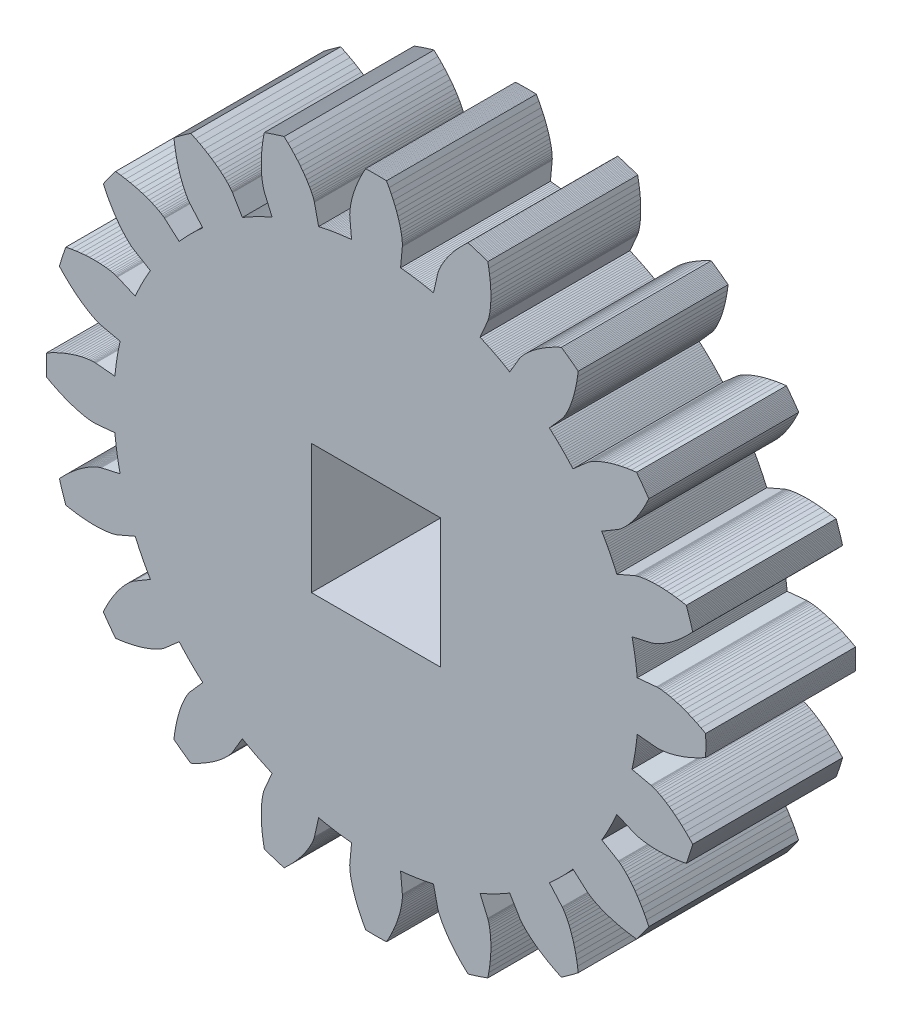
SolidWorks part; units mm, degrees
ref_plane "Front Plane" through (0, 0, 0) normal (0, 0, 1) x (1, 0, 0)
ref_plane "Top Plane" through (0, 0, 0) normal (0, 1, 0) x (1, 0, 0)
ref_plane "Right Plane" through (0, 0, 0) normal (1, 0, 0) x (0, 0, -1)
sketch "Sketch2" plane through (0, 0, 0) normal (0, 0, 1) x (1, 0, 0)
  line L0 (8.7118, -0.8164) -> (9.3559, -0.8768)
  line L1 (9.3559, -0.8768) -> (9.3607, -0.8772)
  line L2 (9.3607, -0.8772) -> (9.3752, -0.8778)
  line L3 (9.3752, -0.8778) -> (9.3993, -0.8781)
  line L4 (9.3993, -0.8781) -> (9.433, -0.8774)
  line L5 (9.433, -0.8774) -> (9.4763, -0.8752)
  line L6 (9.4763, -0.8752) -> (9.5291, -0.8708)
  line L7 (9.5291, -0.8708) -> (9.5914, -0.8636)
  line L8 (9.5914, -0.8636) -> (9.6629, -0.853)
  line L9 (9.6629, -0.853) -> (9.7435, -0.8384)
  line L10 (9.7435, -0.8384) -> (9.833, -0.8192)
  line L11 (9.833, -0.8192) -> (9.9313, -0.7949)
  line L12 (9.9313, -0.7949) -> (10.0379, -0.7648)
  line L13 (10.0379, -0.7648) -> (10.1528, -0.7283)
  line L14 (10.1528, -0.7283) -> (10.2755, -0.6851)
  line L15 (10.2755, -0.6851) -> (10.4057, -0.6344)
  line L16 (10.4057, -0.6344) -> (10.5432, -0.5758)
  line L17 (10.5432, -0.5758) -> (10.6874, -0.5087)
  line L18 (10.6874, -0.5087) -> (10.838, -0.4327)
  line L19 (10.838, -0.4327) -> (10.9945, -0.3474)
  line L20 (10.9945, -0.3474) -> (10.9956, -0.3108)
  line L21 (10.9956, -0.3108) -> (10.9966, -0.2743)
  line L22 (10.9966, -0.2743) -> (10.9974, -0.2377)
  line L23 (10.9974, -0.2377) -> (10.9982, -0.2011)
  line L24 (10.9982, -0.2011) -> (10.9988, -0.1646)
  line L25 (10.9988, -0.1646) -> (10.9993, -0.128)
  line L26 (10.9993, -0.128) -> (10.9996, -0.0914)
  line L27 (10.9996, -0.0914) -> (10.9999, -0.0549)
  line L28 (10.9999, -0.0549) -> (11, -0.0183)
  line L29 (11, -0.0183) -> (11, 0.0183)
  line L30 (11, 0.0183) -> (10.9999, 0.0549)
  line L31 (10.9999, 0.0549) -> (10.9996, 0.0914)
  line L32 (10.9996, 0.0914) -> (10.9993, 0.128)
  line L33 (10.9993, 0.128) -> (10.9988, 0.1646)
  line L34 (10.9988, 0.1646) -> (10.9982, 0.2011)
  line L35 (10.9982, 0.2011) -> (10.9974, 0.2377)
  line L36 (10.9974, 0.2377) -> (10.9966, 0.2743)
  line L37 (10.9966, 0.2743) -> (10.9956, 0.3108)
  line L38 (10.9956, 0.3108) -> (10.9945, 0.3474)
  line L39 (10.9945, 0.3474) -> (10.838, 0.4327)
  line L40 (10.838, 0.4327) -> (10.6874, 0.5087)
  line L41 (10.6874, 0.5087) -> (10.5432, 0.5758)
  line L42 (10.5432, 0.5758) -> (10.4057, 0.6344)
  line L43 (10.4057, 0.6344) -> (10.2755, 0.6851)
  line L44 (10.2755, 0.6851) -> (10.1528, 0.7283)
  line L45 (10.1528, 0.7283) -> (10.0379, 0.7648)
  line L46 (10.0379, 0.7648) -> (9.9313, 0.7949)
  line L47 (9.9313, 0.7949) -> (9.833, 0.8192)
  line L48 (9.833, 0.8192) -> (9.7435, 0.8384)
  line L49 (9.7435, 0.8384) -> (9.6629, 0.853)
  line L50 (9.6629, 0.853) -> (9.5914, 0.8636)
  line L51 (9.5914, 0.8636) -> (9.5291, 0.8708)
  line L52 (9.5291, 0.8708) -> (9.4763, 0.8752)
  line L53 (9.4763, 0.8752) -> (9.433, 0.8774)
  line L54 (9.433, 0.8774) -> (9.3993, 0.8781)
  line L55 (9.3993, 0.8781) -> (9.3752, 0.8778)
  line L56 (9.3752, 0.8778) -> (9.3607, 0.8772)
  line L57 (9.3607, 0.8772) -> (9.3559, 0.8768)
  line L58 (9.3559, 0.8768) -> (8.7118, 0.8164)
  line L59 (8.7118, 0.8164) -> (8.7062, 0.8748)
  line L60 (8.7062, 0.8748) -> (8.7001, 0.9331)
  line L61 (8.7001, 0.9331) -> (8.6937, 0.9913)
  line L62 (8.6937, 0.9913) -> (8.6868, 1.0495)
  line L63 (8.6868, 1.0495) -> (8.6796, 1.1077)
  line L64 (8.6796, 1.1077) -> (8.672, 1.1658)
  line L65 (8.672, 1.1658) -> (8.664, 1.2239)
  line L66 (8.664, 1.2239) -> (8.6556, 1.2819)
  line L67 (8.6556, 1.2819) -> (8.6468, 1.3398)
  line L68 (8.6468, 1.3398) -> (8.6376, 1.3977)
  line L69 (8.6376, 1.3977) -> (8.6281, 1.4556)
  line L70 (8.6281, 1.4556) -> (8.6181, 1.5133)
  line L71 (8.6181, 1.5133) -> (8.6078, 1.571)
  line L72 (8.6078, 1.571) -> (8.5971, 1.6286)
  line L73 (8.5971, 1.6286) -> (8.586, 1.6862)
  line L74 (8.586, 1.6862) -> (8.5745, 1.7437)
  line L75 (8.5745, 1.7437) -> (8.5626, 1.8011)
  line L76 (8.5626, 1.8011) -> (8.5504, 1.8584)
  line L77 (8.5504, 1.8584) -> (8.5377, 1.9156)
  line L78 (8.5377, 1.9156) -> (9.169, 2.0572)
  line L79 (9.169, 2.0572) -> (9.1736, 2.0584)
  line L80 (9.1736, 2.0584) -> (9.1876, 2.0623)
  line L81 (9.1876, 2.0623) -> (9.2106, 2.0694)
  line L82 (9.2106, 2.0694) -> (9.2425, 2.0805)
  line L83 (9.2425, 2.0805) -> (9.283, 2.096)
  line L84 (9.283, 2.096) -> (9.3319, 2.1165)
  line L85 (9.3319, 2.1165) -> (9.3888, 2.1426)
  line L86 (9.3888, 2.1426) -> (9.4535, 2.1747)
  line L87 (9.4535, 2.1747) -> (9.5257, 2.2135)
  line L88 (9.5257, 2.2135) -> (9.6049, 2.2594)
  line L89 (9.6049, 2.2594) -> (9.6908, 2.313)
  line L90 (9.6908, 2.313) -> (9.783, 2.3746)
  line L91 (9.783, 2.3746) -> (9.8809, 2.4447)
  line L92 (9.8809, 2.4447) -> (9.9843, 2.5238)
  line L93 (9.9843, 2.5238) -> (10.0925, 2.6122)
  line L94 (10.0925, 2.6122) -> (10.2051, 2.7104)
  line L95 (10.2051, 2.7104) -> (10.3215, 2.8188)
  line L96 (10.3215, 2.8188) -> (10.4412, 2.9376)
  line L97 (10.4412, 2.9376) -> (10.5638, 3.0671)
  line L98 (10.5638, 3.0671) -> (10.5535, 3.1022)
  line L99 (10.5535, 3.1022) -> (10.5431, 3.1373)
  line L100 (10.5431, 3.1373) -> (10.5326, 3.1723)
  line L101 (10.5326, 3.1723) -> (10.522, 3.2073)
  line L102 (10.522, 3.2073) -> (10.5113, 3.2423)
  line L103 (10.5113, 3.2423) -> (10.5005, 3.2772)
  line L104 (10.5005, 3.2772) -> (10.4895, 3.3121)
  line L105 (10.4895, 3.3121) -> (10.4784, 3.347)
  line L106 (10.4784, 3.347) -> (10.4673, 3.3818)
  line L107 (10.4673, 3.3818) -> (10.456, 3.4166)
  line L108 (10.456, 3.4166) -> (10.4445, 3.4513)
  line L109 (10.4445, 3.4513) -> (10.433, 3.486)
  line L110 (10.433, 3.486) -> (10.4214, 3.5207)
  line L111 (10.4214, 3.5207) -> (10.4096, 3.5553)
  line L112 (10.4096, 3.5553) -> (10.3977, 3.5899)
  line L113 (10.3977, 3.5899) -> (10.3857, 3.6245)
  line L114 (10.3857, 3.6245) -> (10.3736, 3.659)
  line L115 (10.3736, 3.659) -> (10.3614, 3.6934)
  line L116 (10.3614, 3.6934) -> (10.3491, 3.7279)
  line L117 (10.3491, 3.7279) -> (10.1738, 3.7607)
  line L118 (10.1738, 3.7607) -> (10.0071, 3.7864)
  line L119 (10.0071, 3.7864) -> (9.8492, 3.8056)
  line L120 (9.8492, 3.8056) -> (9.7004, 3.8189)
  line L121 (9.7004, 3.8189) -> (9.5609, 3.8268)
  line L122 (9.5609, 3.8268) -> (9.4308, 3.8301)
  line L123 (9.4308, 3.8301) -> (9.3103, 3.8292)
  line L124 (9.3103, 3.8292) -> (9.1996, 3.8249)
  line L125 (9.1996, 3.8249) -> (9.0986, 3.8177)
  line L126 (9.0986, 3.8177) -> (9.0075, 3.8083)
  line L127 (9.0075, 3.8083) -> (8.9264, 3.7973)
  line L128 (8.9264, 3.7973) -> (8.8551, 3.7852)
  line L129 (8.8551, 3.7852) -> (8.7937, 3.7729)
  line L130 (8.7937, 3.7729) -> (8.7421, 3.7607)
  line L131 (8.7421, 3.7607) -> (8.7002, 3.7494)
  line L132 (8.7002, 3.7494) -> (8.6679, 3.7396)
  line L133 (8.6679, 3.7396) -> (8.6451, 3.7319)
  line L134 (8.6451, 3.7319) -> (8.6315, 3.7269)
  line L135 (8.6315, 3.7269) -> (8.6271, 3.725)
  line L136 (8.6271, 3.725) -> (8.0331, 3.4686)
  line L137 (8.0331, 3.4686) -> (8.0097, 3.5223)
  line L138 (8.0097, 3.5223) -> (7.986, 3.5759)
  line L139 (7.986, 3.5759) -> (7.9618, 3.6293)
  line L140 (7.9618, 3.6293) -> (7.9373, 3.6826)
  line L141 (7.9373, 3.6826) -> (7.9125, 3.7356)
  line L142 (7.9125, 3.7356) -> (7.8873, 3.7886)
  line L143 (7.8873, 3.7886) -> (7.8617, 3.8413)
  line L144 (7.8617, 3.8413) -> (7.8358, 3.8939)
  line L145 (7.8358, 3.8939) -> (7.8096, 3.9463)
  line L146 (7.8096, 3.9463) -> (7.783, 3.9985)
  line L147 (7.783, 3.9985) -> (7.756, 4.0506)
  line L148 (7.756, 4.0506) -> (7.7287, 4.1024)
  line L149 (7.7287, 4.1024) -> (7.701, 4.1541)
  line L150 (7.701, 4.1541) -> (7.673, 4.2056)
  line L151 (7.673, 4.2056) -> (7.6447, 4.2569)
  line L152 (7.6447, 4.2569) -> (7.616, 4.308)
  line L153 (7.616, 4.308) -> (7.587, 4.3589)
  line L154 (7.587, 4.3589) -> (7.5576, 4.4096)
  line L155 (7.5576, 4.4096) -> (7.5279, 4.4602)
  line L156 (7.5279, 4.4602) -> (8.0845, 4.7899)
  line L157 (8.0845, 4.7899) -> (8.0886, 4.7925)
  line L158 (8.0886, 4.7925) -> (8.1006, 4.8004)
  line L159 (8.1006, 4.8004) -> (8.1203, 4.8144)
  line L160 (8.1203, 4.8144) -> (8.1472, 4.8347)
  line L161 (8.1472, 4.8347) -> (8.1809, 4.862)
  line L162 (8.1809, 4.862) -> (8.2211, 4.8966)
  line L163 (8.2211, 4.8966) -> (8.2672, 4.939)
  line L164 (8.2672, 4.939) -> (8.3188, 4.9896)
  line L165 (8.3188, 4.9896) -> (8.3755, 5.0488)
  line L166 (8.3755, 5.0488) -> (8.4366, 5.1169)
  line L167 (8.4366, 5.1169) -> (8.5018, 5.1944)
  line L168 (8.5018, 5.1944) -> (8.5704, 5.2815)
  line L169 (8.5704, 5.2815) -> (8.6419, 5.3784)
  line L170 (8.6419, 5.3784) -> (8.7157, 5.4856)
  line L171 (8.7157, 5.4856) -> (8.7913, 5.6031)
  line L172 (8.7913, 5.6031) -> (8.868, 5.7313)
  line L173 (8.868, 5.7313) -> (8.9453, 5.8703)
  line L174 (8.9453, 5.8703) -> (9.0225, 6.0203)
  line L175 (9.0225, 6.0203) -> (9.0989, 6.1814)
  line L176 (9.0989, 6.1814) -> (9.0783, 6.2116)
  line L177 (9.0783, 6.2116) -> (9.0576, 6.2417)
  line L178 (9.0576, 6.2417) -> (9.0368, 6.2718)
  line L179 (9.0368, 6.2718) -> (9.0159, 6.3018)
  line L180 (9.0159, 6.3018) -> (8.9949, 6.3318)
  line L181 (8.9949, 6.3318) -> (8.9738, 6.3616)
  line L182 (8.9738, 6.3616) -> (8.9526, 6.3914)
  line L183 (8.9526, 6.3914) -> (8.9313, 6.4212)
  line L184 (8.9313, 6.4212) -> (8.9099, 6.4508)
  line L185 (8.9099, 6.4508) -> (8.8884, 6.4804)
  line L186 (8.8884, 6.4804) -> (8.8668, 6.5099)
  line L187 (8.8668, 6.5099) -> (8.8451, 6.5394)
  line L188 (8.8451, 6.5394) -> (8.8233, 6.5688)
  line L189 (8.8233, 6.5688) -> (8.8015, 6.5981)
  line L190 (8.8015, 6.5981) -> (8.7795, 6.6273)
  line L191 (8.7795, 6.6273) -> (8.7574, 6.6564)
  line L192 (8.7574, 6.6564) -> (8.7352, 6.6855)
  line L193 (8.7352, 6.6855) -> (8.7129, 6.7145)
  line L194 (8.7129, 6.7145) -> (8.6906, 6.7435)
  line L195 (8.6906, 6.7435) -> (8.5137, 6.7205)
  line L196 (8.5137, 6.7205) -> (8.3472, 6.6934)
  line L197 (8.3472, 6.6934) -> (8.1912, 6.6629)
  line L198 (8.1912, 6.6629) -> (8.0455, 6.6295)
  line L199 (8.0455, 6.6295) -> (7.9104, 6.594)
  line L200 (7.9104, 6.594) -> (7.7857, 6.5569)
  line L201 (7.7857, 6.5569) -> (7.6714, 6.5189)
  line L202 (7.6714, 6.5189) -> (7.5674, 6.4805)
  line L203 (7.5674, 6.4805) -> (7.4736, 6.4425)
  line L204 (7.4736, 6.4425) -> (7.3899, 6.4054)
  line L205 (7.3899, 6.4054) -> (7.3161, 6.3698)
  line L206 (7.3161, 6.3698) -> (7.252, 6.3363)
  line L207 (7.252, 6.3363) -> (7.1974, 6.3056)
  line L208 (7.1974, 6.3056) -> (7.1521, 6.2781)
  line L209 (7.1521, 6.2781) -> (7.1157, 6.2544)
  line L210 (7.1157, 6.2544) -> (7.088, 6.2351)
  line L211 (7.088, 6.2351) -> (7.0687, 6.2207)
  line L212 (7.0687, 6.2207) -> (7.0574, 6.2117)
  line L213 (7.0574, 6.2117) -> (7.0537, 6.2086)
  line L214 (7.0537, 6.2086) -> (6.5681, 5.7812)
  line L215 (6.5681, 5.7812) -> (6.5292, 5.8251)
  line L216 (6.5292, 5.8251) -> (6.4901, 5.8687)
  line L217 (6.4901, 5.8687) -> (6.4506, 5.912)
  line L218 (6.4506, 5.912) -> (6.4109, 5.9551)
  line L219 (6.4109, 5.9551) -> (6.3708, 5.9979)
  line L220 (6.3708, 5.9979) -> (6.3305, 6.0404)
  line L221 (6.3305, 6.0404) -> (6.2899, 6.0827)
  line L222 (6.2899, 6.0827) -> (6.249, 6.1247)
  line L223 (6.249, 6.1247) -> (6.2079, 6.1664)
  line L224 (6.2079, 6.1664) -> (6.1664, 6.2079)
  line L225 (6.1664, 6.2079) -> (6.1247, 6.249)
  line L226 (6.1247, 6.249) -> (6.0827, 6.2899)
  line L227 (6.0827, 6.2899) -> (6.0404, 6.3305)
  line L228 (6.0404, 6.3305) -> (5.9979, 6.3708)
  line L229 (5.9979, 6.3708) -> (5.9551, 6.4109)
  line L230 (5.9551, 6.4109) -> (5.912, 6.4506)
  line L231 (5.912, 6.4506) -> (5.8687, 6.4901)
  line L232 (5.8687, 6.4901) -> (5.8251, 6.5292)
  line L233 (5.8251, 6.5292) -> (5.7812, 6.5681)
  line L234 (5.7812, 6.5681) -> (6.2086, 7.0537)
  line L235 (6.2086, 7.0537) -> (6.2117, 7.0574)
  line L236 (6.2117, 7.0574) -> (6.2207, 7.0687)
  line L237 (6.2207, 7.0687) -> (6.2351, 7.088)
  line L238 (6.2351, 7.088) -> (6.2544, 7.1157)
  line L239 (6.2544, 7.1157) -> (6.2781, 7.1521)
  line L240 (6.2781, 7.1521) -> (6.3056, 7.1974)
  line L241 (6.3056, 7.1974) -> (6.3363, 7.252)
  line L242 (6.3363, 7.252) -> (6.3698, 7.3161)
  line L243 (6.3698, 7.3161) -> (6.4054, 7.3899)
  line L244 (6.4054, 7.3899) -> (6.4425, 7.4736)
  line L245 (6.4425, 7.4736) -> (6.4805, 7.5674)
  line L246 (6.4805, 7.5674) -> (6.5189, 7.6714)
  line L247 (6.5189, 7.6714) -> (6.5569, 7.7857)
  line L248 (6.5569, 7.7857) -> (6.594, 7.9104)
  line L249 (6.594, 7.9104) -> (6.6295, 8.0455)
  line L250 (6.6295, 8.0455) -> (6.6629, 8.1912)
  line L251 (6.6629, 8.1912) -> (6.6934, 8.3472)
  line L252 (6.6934, 8.3472) -> (6.7205, 8.5137)
  line L253 (6.7205, 8.5137) -> (6.7435, 8.6906)
  line L254 (6.7435, 8.6906) -> (6.7145, 8.7129)
  line L255 (6.7145, 8.7129) -> (6.6855, 8.7352)
  line L256 (6.6855, 8.7352) -> (6.6564, 8.7574)
  line L257 (6.6564, 8.7574) -> (6.6273, 8.7795)
  line L258 (6.6273, 8.7795) -> (6.5981, 8.8015)
  line L259 (6.5981, 8.8015) -> (6.5688, 8.8233)
  line L260 (6.5688, 8.8233) -> (6.5394, 8.8451)
  line L261 (6.5394, 8.8451) -> (6.5099, 8.8668)
  line L262 (6.5099, 8.8668) -> (6.4804, 8.8884)
  line L263 (6.4804, 8.8884) -> (6.4508, 8.9099)
  line L264 (6.4508, 8.9099) -> (6.4212, 8.9313)
  line L265 (6.4212, 8.9313) -> (6.3914, 8.9526)
  line L266 (6.3914, 8.9526) -> (6.3616, 8.9738)
  line L267 (6.3616, 8.9738) -> (6.3318, 8.9949)
  line L268 (6.3318, 8.9949) -> (6.3018, 9.0159)
  line L269 (6.3018, 9.0159) -> (6.2718, 9.0368)
  line L270 (6.2718, 9.0368) -> (6.2417, 9.0576)
  line L271 (6.2417, 9.0576) -> (6.2116, 9.0783)
  line L272 (6.2116, 9.0783) -> (6.1814, 9.0989)
  line L273 (6.1814, 9.0989) -> (6.0203, 9.0225)
  line L274 (6.0203, 9.0225) -> (5.8703, 8.9453)
  line L275 (5.8703, 8.9453) -> (5.7313, 8.868)
  line L276 (5.7313, 8.868) -> (5.6031, 8.7913)
  line L277 (5.6031, 8.7913) -> (5.4856, 8.7157)
  line L278 (5.4856, 8.7157) -> (5.3784, 8.6419)
  line L279 (5.3784, 8.6419) -> (5.2815, 8.5704)
  line L280 (5.2815, 8.5704) -> (5.1944, 8.5018)
  line L281 (5.1944, 8.5018) -> (5.1169, 8.4366)
  line L282 (5.1169, 8.4366) -> (5.0488, 8.3755)
  line L283 (5.0488, 8.3755) -> (4.9896, 8.3188)
  line L284 (4.9896, 8.3188) -> (4.939, 8.2672)
  line L285 (4.939, 8.2672) -> (4.8966, 8.2211)
  line L286 (4.8966, 8.2211) -> (4.862, 8.1809)
  line L287 (4.862, 8.1809) -> (4.8347, 8.1472)
  line L288 (4.8347, 8.1472) -> (4.8144, 8.1203)
  line L289 (4.8144, 8.1203) -> (4.8004, 8.1006)
  line L290 (4.8004, 8.1006) -> (4.7925, 8.0886)
  line L291 (4.7925, 8.0886) -> (4.7899, 8.0845)
  line L292 (4.7899, 8.0845) -> (4.4602, 7.5279)
  line L293 (4.4602, 7.5279) -> (4.4096, 7.5576)
  line L294 (4.4096, 7.5576) -> (4.3589, 7.587)
  line L295 (4.3589, 7.587) -> (4.308, 7.616)
  line L296 (4.308, 7.616) -> (4.2569, 7.6447)
  line L297 (4.2569, 7.6447) -> (4.2056, 7.673)
  line L298 (4.2056, 7.673) -> (4.1541, 7.701)
  line L299 (4.1541, 7.701) -> (4.1024, 7.7287)
  line L300 (4.1024, 7.7287) -> (4.0506, 7.756)
  line L301 (4.0506, 7.756) -> (3.9985, 7.783)
  line L302 (3.9985, 7.783) -> (3.9463, 7.8096)
  line L303 (3.9463, 7.8096) -> (3.8939, 7.8358)
  line L304 (3.8939, 7.8358) -> (3.8413, 7.8617)
  line L305 (3.8413, 7.8617) -> (3.7886, 7.8873)
  line L306 (3.7886, 7.8873) -> (3.7356, 7.9125)
  line L307 (3.7356, 7.9125) -> (3.6826, 7.9373)
  line L308 (3.6826, 7.9373) -> (3.6293, 7.9618)
  line L309 (3.6293, 7.9618) -> (3.5759, 7.986)
  line L310 (3.5759, 7.986) -> (3.5223, 8.0097)
  line L311 (3.5223, 8.0097) -> (3.4686, 8.0331)
  line L312 (3.4686, 8.0331) -> (3.725, 8.6271)
  line L313 (3.725, 8.6271) -> (3.7269, 8.6315)
  line L314 (3.7269, 8.6315) -> (3.7319, 8.6451)
  line L315 (3.7319, 8.6451) -> (3.7396, 8.6679)
  line L316 (3.7396, 8.6679) -> (3.7494, 8.7002)
  line L317 (3.7494, 8.7002) -> (3.7607, 8.7421)
  line L318 (3.7607, 8.7421) -> (3.7729, 8.7937)
  line L319 (3.7729, 8.7937) -> (3.7852, 8.8551)
  line L320 (3.7852, 8.8551) -> (3.7973, 8.9264)
  line L321 (3.7973, 8.9264) -> (3.8083, 9.0075)
  line L322 (3.8083, 9.0075) -> (3.8177, 9.0986)
  line L323 (3.8177, 9.0986) -> (3.8249, 9.1996)
  line L324 (3.8249, 9.1996) -> (3.8292, 9.3103)
  line L325 (3.8292, 9.3103) -> (3.8301, 9.4308)
  line L326 (3.8301, 9.4308) -> (3.8268, 9.5609)
  line L327 (3.8268, 9.5609) -> (3.8189, 9.7004)
  line L328 (3.8189, 9.7004) -> (3.8056, 9.8492)
  line L329 (3.8056, 9.8492) -> (3.7864, 10.0071)
  line L330 (3.7864, 10.0071) -> (3.7607, 10.1738)
  line L331 (3.7607, 10.1738) -> (3.7279, 10.3491)
  line L332 (3.7279, 10.3491) -> (3.6934, 10.3614)
  line L333 (3.6934, 10.3614) -> (3.659, 10.3736)
  line L334 (3.659, 10.3736) -> (3.6245, 10.3857)
  line L335 (3.6245, 10.3857) -> (3.5899, 10.3977)
  line L336 (3.5899, 10.3977) -> (3.5553, 10.4096)
  line L337 (3.5553, 10.4096) -> (3.5207, 10.4214)
  line L338 (3.5207, 10.4214) -> (3.486, 10.433)
  line L339 (3.486, 10.433) -> (3.4513, 10.4445)
  line L340 (3.4513, 10.4445) -> (3.4166, 10.456)
  line L341 (3.4166, 10.456) -> (3.3818, 10.4673)
  line L342 (3.3818, 10.4673) -> (3.347, 10.4784)
  line L343 (3.347, 10.4784) -> (3.3121, 10.4895)
  line L344 (3.3121, 10.4895) -> (3.2772, 10.5005)
  line L345 (3.2772, 10.5005) -> (3.2423, 10.5113)
  line L346 (3.2423, 10.5113) -> (3.2073, 10.522)
  line L347 (3.2073, 10.522) -> (3.1723, 10.5326)
  line L348 (3.1723, 10.5326) -> (3.1373, 10.5431)
  line L349 (3.1373, 10.5431) -> (3.1022, 10.5535)
  line L350 (3.1022, 10.5535) -> (3.0671, 10.5638)
  line L351 (3.0671, 10.5638) -> (2.9376, 10.4412)
  line L352 (2.9376, 10.4412) -> (2.8188, 10.3215)
  line L353 (2.8188, 10.3215) -> (2.7104, 10.2051)
  line L354 (2.7104, 10.2051) -> (2.6122, 10.0925)
  line L355 (2.6122, 10.0925) -> (2.5238, 9.9843)
  line L356 (2.5238, 9.9843) -> (2.4447, 9.8809)
  line L357 (2.4447, 9.8809) -> (2.3746, 9.783)
  line L358 (2.3746, 9.783) -> (2.313, 9.6908)
  line L359 (2.313, 9.6908) -> (2.2594, 9.6049)
  line L360 (2.2594, 9.6049) -> (2.2135, 9.5257)
  line L361 (2.2135, 9.5257) -> (2.1747, 9.4535)
  line L362 (2.1747, 9.4535) -> (2.1426, 9.3888)
  line L363 (2.1426, 9.3888) -> (2.1165, 9.3319)
  line L364 (2.1165, 9.3319) -> (2.096, 9.283)
  line L365 (2.096, 9.283) -> (2.0805, 9.2425)
  line L366 (2.0805, 9.2425) -> (2.0694, 9.2106)
  line L367 (2.0694, 9.2106) -> (2.0623, 9.1876)
  line L368 (2.0623, 9.1876) -> (2.0584, 9.1736)
  line L369 (2.0584, 9.1736) -> (2.0572, 9.169)
  line L370 (2.0572, 9.169) -> (1.9156, 8.5377)
  line L371 (1.9156, 8.5377) -> (1.8584, 8.5504)
  line L372 (1.8584, 8.5504) -> (1.8011, 8.5626)
  line L373 (1.8011, 8.5626) -> (1.7437, 8.5745)
  line L374 (1.7437, 8.5745) -> (1.6862, 8.586)
  line L375 (1.6862, 8.586) -> (1.6286, 8.5971)
  line L376 (1.6286, 8.5971) -> (1.571, 8.6078)
  line L377 (1.571, 8.6078) -> (1.5133, 8.6181)
  line L378 (1.5133, 8.6181) -> (1.4556, 8.6281)
  line L379 (1.4556, 8.6281) -> (1.3977, 8.6376)
  line L380 (1.3977, 8.6376) -> (1.3398, 8.6468)
  line L381 (1.3398, 8.6468) -> (1.2819, 8.6556)
  line L382 (1.2819, 8.6556) -> (1.2239, 8.664)
  line L383 (1.2239, 8.664) -> (1.1658, 8.672)
  line L384 (1.1658, 8.672) -> (1.1077, 8.6796)
  line L385 (1.1077, 8.6796) -> (1.0495, 8.6868)
  line L386 (1.0495, 8.6868) -> (0.9913, 8.6937)
  line L387 (0.9913, 8.6937) -> (0.9331, 8.7001)
  line L388 (0.9331, 8.7001) -> (0.8748, 8.7062)
  line L389 (0.8748, 8.7062) -> (0.8164, 8.7118)
  line L390 (0.8164, 8.7118) -> (0.8768, 9.3559)
  line L391 (0.8768, 9.3559) -> (0.8772, 9.3607)
  line L392 (0.8772, 9.3607) -> (0.8778, 9.3752)
  line L393 (0.8778, 9.3752) -> (0.8781, 9.3993)
  line L394 (0.8781, 9.3993) -> (0.8774, 9.433)
  line L395 (0.8774, 9.433) -> (0.8752, 9.4763)
  line L396 (0.8752, 9.4763) -> (0.8708, 9.5291)
  line L397 (0.8708, 9.5291) -> (0.8636, 9.5914)
  line L398 (0.8636, 9.5914) -> (0.853, 9.6629)
  line L399 (0.853, 9.6629) -> (0.8384, 9.7435)
  line L400 (0.8384, 9.7435) -> (0.8192, 9.833)
  line L401 (0.8192, 9.833) -> (0.7949, 9.9313)
  line L402 (0.7949, 9.9313) -> (0.7648, 10.0379)
  line L403 (0.7648, 10.0379) -> (0.7283, 10.1528)
  line L404 (0.7283, 10.1528) -> (0.6851, 10.2755)
  line L405 (0.6851, 10.2755) -> (0.6344, 10.4057)
  line L406 (0.6344, 10.4057) -> (0.5758, 10.5432)
  line L407 (0.5758, 10.5432) -> (0.5087, 10.6874)
  line L408 (0.5087, 10.6874) -> (0.4327, 10.838)
  line L409 (0.4327, 10.838) -> (0.3474, 10.9945)
  line L410 (0.3474, 10.9945) -> (0.3108, 10.9956)
  line L411 (0.3108, 10.9956) -> (0.2743, 10.9966)
  line L412 (0.2743, 10.9966) -> (0.2377, 10.9974)
  line L413 (0.2377, 10.9974) -> (0.2011, 10.9982)
  line L414 (0.2011, 10.9982) -> (0.1646, 10.9988)
  line L415 (0.1646, 10.9988) -> (0.128, 10.9993)
  line L416 (0.128, 10.9993) -> (0.0914, 10.9996)
  line L417 (0.0914, 10.9996) -> (0.0549, 10.9999)
  line L418 (0.0549, 10.9999) -> (0.0183, 11)
  line L419 (0.0183, 11) -> (-0.0183, 11)
  line L420 (-0.0183, 11) -> (-0.0549, 10.9999)
  line L421 (-0.0549, 10.9999) -> (-0.0914, 10.9996)
  line L422 (-0.0914, 10.9996) -> (-0.128, 10.9993)
  line L423 (-0.128, 10.9993) -> (-0.1646, 10.9988)
  line L424 (-0.1646, 10.9988) -> (-0.2011, 10.9982)
  line L425 (-0.2011, 10.9982) -> (-0.2377, 10.9974)
  line L426 (-0.2377, 10.9974) -> (-0.2743, 10.9966)
  line L427 (-0.2743, 10.9966) -> (-0.3108, 10.9956)
  line L428 (-0.3108, 10.9956) -> (-0.3474, 10.9945)
  line L429 (-0.3474, 10.9945) -> (-0.4327, 10.838)
  line L430 (-0.4327, 10.838) -> (-0.5087, 10.6874)
  line L431 (-0.5087, 10.6874) -> (-0.5758, 10.5432)
  line L432 (-0.5758, 10.5432) -> (-0.6344, 10.4057)
  line L433 (-0.6344, 10.4057) -> (-0.6851, 10.2755)
  line L434 (-0.6851, 10.2755) -> (-0.7283, 10.1528)
  line L435 (-0.7283, 10.1528) -> (-0.7648, 10.0379)
  line L436 (-0.7648, 10.0379) -> (-0.7949, 9.9313)
  line L437 (-0.7949, 9.9313) -> (-0.8192, 9.833)
  line L438 (-0.8192, 9.833) -> (-0.8384, 9.7435)
  line L439 (-0.8384, 9.7435) -> (-0.853, 9.6629)
  line L440 (-0.853, 9.6629) -> (-0.8636, 9.5914)
  line L441 (-0.8636, 9.5914) -> (-0.8708, 9.5291)
  line L442 (-0.8708, 9.5291) -> (-0.8752, 9.4763)
  line L443 (-0.8752, 9.4763) -> (-0.8774, 9.433)
  line L444 (-0.8774, 9.433) -> (-0.8781, 9.3993)
  line L445 (-0.8781, 9.3993) -> (-0.8778, 9.3752)
  line L446 (-0.8778, 9.3752) -> (-0.8772, 9.3607)
  line L447 (-0.8772, 9.3607) -> (-0.8768, 9.3559)
  line L448 (-0.8768, 9.3559) -> (-0.8164, 8.7118)
  line L449 (-0.8164, 8.7118) -> (-0.8748, 8.7062)
  line L450 (-0.8748, 8.7062) -> (-0.9331, 8.7001)
  line L451 (-0.9331, 8.7001) -> (-0.9913, 8.6937)
  line L452 (-0.9913, 8.6937) -> (-1.0495, 8.6868)
  line L453 (-1.0495, 8.6868) -> (-1.1077, 8.6796)
  line L454 (-1.1077, 8.6796) -> (-1.1658, 8.672)
  line L455 (-1.1658, 8.672) -> (-1.2239, 8.664)
  line L456 (-1.2239, 8.664) -> (-1.2819, 8.6556)
  line L457 (-1.2819, 8.6556) -> (-1.3398, 8.6468)
  line L458 (-1.3398, 8.6468) -> (-1.3977, 8.6376)
  line L459 (-1.3977, 8.6376) -> (-1.4556, 8.6281)
  line L460 (-1.4556, 8.6281) -> (-1.5133, 8.6181)
  line L461 (-1.5133, 8.6181) -> (-1.571, 8.6078)
  line L462 (-1.571, 8.6078) -> (-1.6286, 8.5971)
  line L463 (-1.6286, 8.5971) -> (-1.6862, 8.586)
  line L464 (-1.6862, 8.586) -> (-1.7437, 8.5745)
  line L465 (-1.7437, 8.5745) -> (-1.8011, 8.5626)
  line L466 (-1.8011, 8.5626) -> (-1.8584, 8.5504)
  line L467 (-1.8584, 8.5504) -> (-1.9156, 8.5377)
  line L468 (-1.9156, 8.5377) -> (-2.0572, 9.169)
  line L469 (-2.0572, 9.169) -> (-2.0584, 9.1736)
  line L470 (-2.0584, 9.1736) -> (-2.0623, 9.1876)
  line L471 (-2.0623, 9.1876) -> (-2.0694, 9.2106)
  line L472 (-2.0694, 9.2106) -> (-2.0805, 9.2425)
  line L473 (-2.0805, 9.2425) -> (-2.096, 9.283)
  line L474 (-2.096, 9.283) -> (-2.1165, 9.3319)
  line L475 (-2.1165, 9.3319) -> (-2.1426, 9.3888)
  line L476 (-2.1426, 9.3888) -> (-2.1747, 9.4535)
  line L477 (-2.1747, 9.4535) -> (-2.2135, 9.5257)
  line L478 (-2.2135, 9.5257) -> (-2.2594, 9.6049)
  line L479 (-2.2594, 9.6049) -> (-2.313, 9.6908)
  line L480 (-2.313, 9.6908) -> (-2.3746, 9.783)
  line L481 (-2.3746, 9.783) -> (-2.4447, 9.8809)
  line L482 (-2.4447, 9.8809) -> (-2.5238, 9.9843)
  line L483 (-2.5238, 9.9843) -> (-2.6122, 10.0925)
  line L484 (-2.6122, 10.0925) -> (-2.7104, 10.2051)
  line L485 (-2.7104, 10.2051) -> (-2.8188, 10.3215)
  line L486 (-2.8188, 10.3215) -> (-2.9376, 10.4412)
  line L487 (-2.9376, 10.4412) -> (-3.0671, 10.5638)
  line L488 (-3.0671, 10.5638) -> (-3.1022, 10.5535)
  line L489 (-3.1022, 10.5535) -> (-3.1373, 10.5431)
  line L490 (-3.1373, 10.5431) -> (-3.1723, 10.5326)
  line L491 (-3.1723, 10.5326) -> (-3.2073, 10.522)
  line L492 (-3.2073, 10.522) -> (-3.2423, 10.5113)
  line L493 (-3.2423, 10.5113) -> (-3.2772, 10.5005)
  line L494 (-3.2772, 10.5005) -> (-3.3121, 10.4895)
  line L495 (-3.3121, 10.4895) -> (-3.347, 10.4784)
  line L496 (-3.347, 10.4784) -> (-3.3818, 10.4673)
  line L497 (-3.3818, 10.4673) -> (-3.4166, 10.456)
  line L498 (-3.4166, 10.456) -> (-3.4513, 10.4445)
  line L499 (-3.4513, 10.4445) -> (-3.486, 10.433)
  line L500 (-3.486, 10.433) -> (-3.5207, 10.4214)
  line L501 (-3.5207, 10.4214) -> (-3.5553, 10.4096)
  line L502 (-3.5553, 10.4096) -> (-3.5899, 10.3977)
  line L503 (-3.5899, 10.3977) -> (-3.6245, 10.3857)
  line L504 (-3.6245, 10.3857) -> (-3.659, 10.3736)
  line L505 (-3.659, 10.3736) -> (-3.6934, 10.3614)
  line L506 (-3.6934, 10.3614) -> (-3.7279, 10.3491)
  line L507 (-3.7279, 10.3491) -> (-3.7607, 10.1738)
  line L508 (-3.7607, 10.1738) -> (-3.7864, 10.0071)
  line L509 (-3.7864, 10.0071) -> (-3.8056, 9.8492)
  line L510 (-3.8056, 9.8492) -> (-3.8189, 9.7004)
  line L511 (-3.8189, 9.7004) -> (-3.8268, 9.5609)
  line L512 (-3.8268, 9.5609) -> (-3.8301, 9.4308)
  line L513 (-3.8301, 9.4308) -> (-3.8292, 9.3103)
  line L514 (-3.8292, 9.3103) -> (-3.8249, 9.1996)
  line L515 (-3.8249, 9.1996) -> (-3.8177, 9.0986)
  line L516 (-3.8177, 9.0986) -> (-3.8083, 9.0075)
  line L517 (-3.8083, 9.0075) -> (-3.7973, 8.9264)
  line L518 (-3.7973, 8.9264) -> (-3.7852, 8.8551)
  line L519 (-3.7852, 8.8551) -> (-3.7729, 8.7937)
  line L520 (-3.7729, 8.7937) -> (-3.7607, 8.7421)
  line L521 (-3.7607, 8.7421) -> (-3.7494, 8.7002)
  line L522 (-3.7494, 8.7002) -> (-3.7396, 8.6679)
  line L523 (-3.7396, 8.6679) -> (-3.7319, 8.6451)
  line L524 (-3.7319, 8.6451) -> (-3.7269, 8.6315)
  line L525 (-3.7269, 8.6315) -> (-3.725, 8.6271)
  line L526 (-3.725, 8.6271) -> (-3.4686, 8.0331)
  line L527 (-3.4686, 8.0331) -> (-3.5223, 8.0097)
  line L528 (-3.5223, 8.0097) -> (-3.5759, 7.986)
  line L529 (-3.5759, 7.986) -> (-3.6293, 7.9618)
  line L530 (-3.6293, 7.9618) -> (-3.6826, 7.9373)
  line L531 (-3.6826, 7.9373) -> (-3.7356, 7.9125)
  line L532 (-3.7356, 7.9125) -> (-3.7886, 7.8873)
  line L533 (-3.7886, 7.8873) -> (-3.8413, 7.8617)
  line L534 (-3.8413, 7.8617) -> (-3.8939, 7.8358)
  line L535 (-3.8939, 7.8358) -> (-3.9463, 7.8096)
  line L536 (-3.9463, 7.8096) -> (-3.9985, 7.783)
  line L537 (-3.9985, 7.783) -> (-4.0506, 7.756)
  line L538 (-4.0506, 7.756) -> (-4.1024, 7.7287)
  line L539 (-4.1024, 7.7287) -> (-4.1541, 7.701)
  line L540 (-4.1541, 7.701) -> (-4.2056, 7.673)
  line L541 (-4.2056, 7.673) -> (-4.2569, 7.6447)
  line L542 (-4.2569, 7.6447) -> (-4.308, 7.616)
  line L543 (-4.308, 7.616) -> (-4.3589, 7.587)
  line L544 (-4.3589, 7.587) -> (-4.4096, 7.5576)
  line L545 (-4.4096, 7.5576) -> (-4.4602, 7.5279)
  line L546 (-4.4602, 7.5279) -> (-4.7899, 8.0845)
  line L547 (-4.7899, 8.0845) -> (-4.7925, 8.0886)
  line L548 (-4.7925, 8.0886) -> (-4.8004, 8.1006)
  line L549 (-4.8004, 8.1006) -> (-4.8144, 8.1203)
  line L550 (-4.8144, 8.1203) -> (-4.8347, 8.1472)
  line L551 (-4.8347, 8.1472) -> (-4.862, 8.1809)
  line L552 (-4.862, 8.1809) -> (-4.8966, 8.2211)
  line L553 (-4.8966, 8.2211) -> (-4.939, 8.2672)
  line L554 (-4.939, 8.2672) -> (-4.9896, 8.3188)
  line L555 (-4.9896, 8.3188) -> (-5.0488, 8.3755)
  line L556 (-5.0488, 8.3755) -> (-5.1169, 8.4366)
  line L557 (-5.1169, 8.4366) -> (-5.1944, 8.5018)
  line L558 (-5.1944, 8.5018) -> (-5.2815, 8.5704)
  line L559 (-5.2815, 8.5704) -> (-5.3784, 8.6419)
  line L560 (-5.3784, 8.6419) -> (-5.4856, 8.7157)
  line L561 (-5.4856, 8.7157) -> (-5.6031, 8.7913)
  line L562 (-5.6031, 8.7913) -> (-5.7313, 8.868)
  line L563 (-5.7313, 8.868) -> (-5.8703, 8.9453)
  line L564 (-5.8703, 8.9453) -> (-6.0203, 9.0225)
  line L565 (-6.0203, 9.0225) -> (-6.1814, 9.0989)
  line L566 (-6.1814, 9.0989) -> (-6.2116, 9.0783)
  line L567 (-6.2116, 9.0783) -> (-6.2417, 9.0576)
  line L568 (-6.2417, 9.0576) -> (-6.2718, 9.0368)
  line L569 (-6.2718, 9.0368) -> (-6.3018, 9.0159)
  line L570 (-6.3018, 9.0159) -> (-6.3318, 8.9949)
  line L571 (-6.3318, 8.9949) -> (-6.3616, 8.9738)
  line L572 (-6.3616, 8.9738) -> (-6.3914, 8.9526)
  line L573 (-6.3914, 8.9526) -> (-6.4212, 8.9313)
  line L574 (-6.4212, 8.9313) -> (-6.4508, 8.9099)
  line L575 (-6.4508, 8.9099) -> (-6.4804, 8.8884)
  line L576 (-6.4804, 8.8884) -> (-6.5099, 8.8668)
  line L577 (-6.5099, 8.8668) -> (-6.5394, 8.8451)
  line L578 (-6.5394, 8.8451) -> (-6.5688, 8.8233)
  line L579 (-6.5688, 8.8233) -> (-6.5981, 8.8015)
  line L580 (-6.5981, 8.8015) -> (-6.6273, 8.7795)
  line L581 (-6.6273, 8.7795) -> (-6.6564, 8.7574)
  line L582 (-6.6564, 8.7574) -> (-6.6855, 8.7352)
  line L583 (-6.6855, 8.7352) -> (-6.7145, 8.7129)
  line L584 (-6.7145, 8.7129) -> (-6.7435, 8.6906)
  line L585 (-6.7435, 8.6906) -> (-6.7205, 8.5137)
  line L586 (-6.7205, 8.5137) -> (-6.6934, 8.3472)
  line L587 (-6.6934, 8.3472) -> (-6.6629, 8.1912)
  line L588 (-6.6629, 8.1912) -> (-6.6295, 8.0455)
  line L589 (-6.6295, 8.0455) -> (-6.594, 7.9104)
  line L590 (-6.594, 7.9104) -> (-6.5569, 7.7857)
  line L591 (-6.5569, 7.7857) -> (-6.5189, 7.6714)
  line L592 (-6.5189, 7.6714) -> (-6.4805, 7.5674)
  line L593 (-6.4805, 7.5674) -> (-6.4425, 7.4736)
  line L594 (-6.4425, 7.4736) -> (-6.4054, 7.3899)
  line L595 (-6.4054, 7.3899) -> (-6.3698, 7.3161)
  line L596 (-6.3698, 7.3161) -> (-6.3363, 7.252)
  line L597 (-6.3363, 7.252) -> (-6.3056, 7.1974)
  line L598 (-6.3056, 7.1974) -> (-6.2781, 7.1521)
  line L599 (-6.2781, 7.1521) -> (-6.2544, 7.1157)
  line L600 (-6.2544, 7.1157) -> (-6.2351, 7.088)
  line L601 (-6.2351, 7.088) -> (-6.2207, 7.0687)
  line L602 (-6.2207, 7.0687) -> (-6.2117, 7.0574)
  line L603 (-6.2117, 7.0574) -> (-6.2086, 7.0537)
  line L604 (-6.2086, 7.0537) -> (-5.7812, 6.5681)
  line L605 (-5.7812, 6.5681) -> (-5.8251, 6.5292)
  line L606 (-5.8251, 6.5292) -> (-5.8687, 6.4901)
  line L607 (-5.8687, 6.4901) -> (-5.912, 6.4506)
  line L608 (-5.912, 6.4506) -> (-5.9551, 6.4109)
  line L609 (-5.9551, 6.4109) -> (-5.9979, 6.3708)
  line L610 (-5.9979, 6.3708) -> (-6.0404, 6.3305)
  line L611 (-6.0404, 6.3305) -> (-6.0827, 6.2899)
  line L612 (-6.0827, 6.2899) -> (-6.1247, 6.249)
  line L613 (-6.1247, 6.249) -> (-6.1664, 6.2079)
  line L614 (-6.1664, 6.2079) -> (-6.2079, 6.1664)
  line L615 (-6.2079, 6.1664) -> (-6.249, 6.1247)
  line L616 (-6.249, 6.1247) -> (-6.2899, 6.0827)
  line L617 (-6.2899, 6.0827) -> (-6.3305, 6.0404)
  line L618 (-6.3305, 6.0404) -> (-6.3708, 5.9979)
  line L619 (-6.3708, 5.9979) -> (-6.4109, 5.9551)
  line L620 (-6.4109, 5.9551) -> (-6.4506, 5.912)
  line L621 (-6.4506, 5.912) -> (-6.4901, 5.8687)
  line L622 (-6.4901, 5.8687) -> (-6.5292, 5.8251)
  line L623 (-6.5292, 5.8251) -> (-6.5681, 5.7812)
  line L624 (-6.5681, 5.7812) -> (-7.0537, 6.2086)
  line L625 (-7.0537, 6.2086) -> (-7.0574, 6.2117)
  line L626 (-7.0574, 6.2117) -> (-7.0687, 6.2207)
  line L627 (-7.0687, 6.2207) -> (-7.088, 6.2351)
  line L628 (-7.088, 6.2351) -> (-7.1157, 6.2544)
  line L629 (-7.1157, 6.2544) -> (-7.1521, 6.2781)
  line L630 (-7.1521, 6.2781) -> (-7.1974, 6.3056)
  line L631 (-7.1974, 6.3056) -> (-7.252, 6.3363)
  line L632 (-7.252, 6.3363) -> (-7.3161, 6.3698)
  line L633 (-7.3161, 6.3698) -> (-7.3899, 6.4054)
  line L634 (-7.3899, 6.4054) -> (-7.4736, 6.4425)
  line L635 (-7.4736, 6.4425) -> (-7.5674, 6.4805)
  line L636 (-7.5674, 6.4805) -> (-7.6714, 6.5189)
  line L637 (-7.6714, 6.5189) -> (-7.7857, 6.5569)
  line L638 (-7.7857, 6.5569) -> (-7.9104, 6.594)
  line L639 (-7.9104, 6.594) -> (-8.0455, 6.6295)
  line L640 (-8.0455, 6.6295) -> (-8.1912, 6.6629)
  line L641 (-8.1912, 6.6629) -> (-8.3472, 6.6934)
  line L642 (-8.3472, 6.6934) -> (-8.5137, 6.7205)
  line L643 (-8.5137, 6.7205) -> (-8.6906, 6.7435)
  line L644 (-8.6906, 6.7435) -> (-8.7129, 6.7145)
  line L645 (-8.7129, 6.7145) -> (-8.7352, 6.6855)
  line L646 (-8.7352, 6.6855) -> (-8.7574, 6.6564)
  line L647 (-8.7574, 6.6564) -> (-8.7795, 6.6273)
  line L648 (-8.7795, 6.6273) -> (-8.8015, 6.5981)
  line L649 (-8.8015, 6.5981) -> (-8.8233, 6.5688)
  line L650 (-8.8233, 6.5688) -> (-8.8451, 6.5394)
  line L651 (-8.8451, 6.5394) -> (-8.8668, 6.5099)
  line L652 (-8.8668, 6.5099) -> (-8.8884, 6.4804)
  line L653 (-8.8884, 6.4804) -> (-8.9099, 6.4508)
  line L654 (-8.9099, 6.4508) -> (-8.9313, 6.4212)
  line L655 (-8.9313, 6.4212) -> (-8.9526, 6.3914)
  line L656 (-8.9526, 6.3914) -> (-8.9738, 6.3616)
  line L657 (-8.9738, 6.3616) -> (-8.9949, 6.3318)
  line L658 (-8.9949, 6.3318) -> (-9.0159, 6.3018)
  line L659 (-9.0159, 6.3018) -> (-9.0368, 6.2718)
  line L660 (-9.0368, 6.2718) -> (-9.0576, 6.2417)
  line L661 (-9.0576, 6.2417) -> (-9.0783, 6.2116)
  line L662 (-9.0783, 6.2116) -> (-9.0989, 6.1814)
  line L663 (-9.0989, 6.1814) -> (-9.0225, 6.0203)
  line L664 (-9.0225, 6.0203) -> (-8.9453, 5.8703)
  line L665 (-8.9453, 5.8703) -> (-8.868, 5.7313)
  line L666 (-8.868, 5.7313) -> (-8.7913, 5.6031)
  line L667 (-8.7913, 5.6031) -> (-8.7157, 5.4856)
  line L668 (-8.7157, 5.4856) -> (-8.6419, 5.3784)
  line L669 (-8.6419, 5.3784) -> (-8.5704, 5.2815)
  line L670 (-8.5704, 5.2815) -> (-8.5018, 5.1944)
  line L671 (-8.5018, 5.1944) -> (-8.4366, 5.1169)
  line L672 (-8.4366, 5.1169) -> (-8.3755, 5.0488)
  line L673 (-8.3755, 5.0488) -> (-8.3188, 4.9896)
  line L674 (-8.3188, 4.9896) -> (-8.2672, 4.939)
  line L675 (-8.2672, 4.939) -> (-8.2211, 4.8966)
  line L676 (-8.2211, 4.8966) -> (-8.1809, 4.862)
  line L677 (-8.1809, 4.862) -> (-8.1472, 4.8347)
  line L678 (-8.1472, 4.8347) -> (-8.1203, 4.8144)
  line L679 (-8.1203, 4.8144) -> (-8.1006, 4.8004)
  line L680 (-8.1006, 4.8004) -> (-8.0886, 4.7925)
  line L681 (-8.0886, 4.7925) -> (-8.0845, 4.7899)
  line L682 (-8.0845, 4.7899) -> (-7.5279, 4.4602)
  line L683 (-7.5279, 4.4602) -> (-7.5576, 4.4096)
  line L684 (-7.5576, 4.4096) -> (-7.587, 4.3589)
  line L685 (-7.587, 4.3589) -> (-7.616, 4.308)
  line L686 (-7.616, 4.308) -> (-7.6447, 4.2569)
  line L687 (-7.6447, 4.2569) -> (-7.673, 4.2056)
  line L688 (-7.673, 4.2056) -> (-7.701, 4.1541)
  line L689 (-7.701, 4.1541) -> (-7.7287, 4.1024)
  line L690 (-7.7287, 4.1024) -> (-7.756, 4.0506)
  line L691 (-7.756, 4.0506) -> (-7.783, 3.9985)
  line L692 (-7.783, 3.9985) -> (-7.8096, 3.9463)
  line L693 (-7.8096, 3.9463) -> (-7.8358, 3.8939)
  line L694 (-7.8358, 3.8939) -> (-7.8617, 3.8413)
  line L695 (-7.8617, 3.8413) -> (-7.8873, 3.7886)
  line L696 (-7.8873, 3.7886) -> (-7.9125, 3.7356)
  line L697 (-7.9125, 3.7356) -> (-7.9373, 3.6826)
  line L698 (-7.9373, 3.6826) -> (-7.9618, 3.6293)
  line L699 (-7.9618, 3.6293) -> (-7.986, 3.5759)
  line L700 (-7.986, 3.5759) -> (-8.0097, 3.5223)
  line L701 (-8.0097, 3.5223) -> (-8.0331, 3.4686)
  line L702 (-8.0331, 3.4686) -> (-8.6271, 3.725)
  line L703 (-8.6271, 3.725) -> (-8.6315, 3.7269)
  line L704 (-8.6315, 3.7269) -> (-8.6451, 3.7319)
  line L705 (-8.6451, 3.7319) -> (-8.6679, 3.7396)
  line L706 (-8.6679, 3.7396) -> (-8.7002, 3.7494)
  line L707 (-8.7002, 3.7494) -> (-8.7421, 3.7607)
  line L708 (-8.7421, 3.7607) -> (-8.7937, 3.7729)
  line L709 (-8.7937, 3.7729) -> (-8.8551, 3.7852)
  line L710 (-8.8551, 3.7852) -> (-8.9264, 3.7973)
  line L711 (-8.9264, 3.7973) -> (-9.0075, 3.8083)
  line L712 (-9.0075, 3.8083) -> (-9.0986, 3.8177)
  line L713 (-9.0986, 3.8177) -> (-9.1996, 3.8249)
  line L714 (-9.1996, 3.8249) -> (-9.3103, 3.8292)
  line L715 (-9.3103, 3.8292) -> (-9.4308, 3.8301)
  line L716 (-9.4308, 3.8301) -> (-9.5609, 3.8268)
  line L717 (-9.5609, 3.8268) -> (-9.7004, 3.8189)
  line L718 (-9.7004, 3.8189) -> (-9.8492, 3.8056)
  line L719 (-9.8492, 3.8056) -> (-10.0071, 3.7864)
  line L720 (-10.0071, 3.7864) -> (-10.1738, 3.7607)
  line L721 (-10.1738, 3.7607) -> (-10.3491, 3.7279)
  line L722 (-10.3491, 3.7279) -> (-10.3614, 3.6934)
  line L723 (-10.3614, 3.6934) -> (-10.3736, 3.659)
  line L724 (-10.3736, 3.659) -> (-10.3857, 3.6245)
  line L725 (-10.3857, 3.6245) -> (-10.3977, 3.5899)
  line L726 (-10.3977, 3.5899) -> (-10.4096, 3.5553)
  line L727 (-10.4096, 3.5553) -> (-10.4214, 3.5207)
  line L728 (-10.4214, 3.5207) -> (-10.433, 3.486)
  line L729 (-10.433, 3.486) -> (-10.4445, 3.4513)
  line L730 (-10.4445, 3.4513) -> (-10.456, 3.4166)
  line L731 (-10.456, 3.4166) -> (-10.4673, 3.3818)
  line L732 (-10.4673, 3.3818) -> (-10.4784, 3.347)
  line L733 (-10.4784, 3.347) -> (-10.4895, 3.3121)
  line L734 (-10.4895, 3.3121) -> (-10.5005, 3.2772)
  line L735 (-10.5005, 3.2772) -> (-10.5113, 3.2423)
  line L736 (-10.5113, 3.2423) -> (-10.522, 3.2073)
  line L737 (-10.522, 3.2073) -> (-10.5326, 3.1723)
  line L738 (-10.5326, 3.1723) -> (-10.5431, 3.1373)
  line L739 (-10.5431, 3.1373) -> (-10.5535, 3.1022)
  line L740 (-10.5535, 3.1022) -> (-10.5638, 3.0671)
  line L741 (-10.5638, 3.0671) -> (-10.4412, 2.9376)
  line L742 (-10.4412, 2.9376) -> (-10.3215, 2.8188)
  line L743 (-10.3215, 2.8188) -> (-10.2051, 2.7104)
  line L744 (-10.2051, 2.7104) -> (-10.0925, 2.6122)
  line L745 (-10.0925, 2.6122) -> (-9.9843, 2.5238)
  line L746 (-9.9843, 2.5238) -> (-9.8809, 2.4447)
  line L747 (-9.8809, 2.4447) -> (-9.783, 2.3746)
  line L748 (-9.783, 2.3746) -> (-9.6908, 2.313)
  line L749 (-9.6908, 2.313) -> (-9.6049, 2.2594)
  line L750 (-9.6049, 2.2594) -> (-9.5257, 2.2135)
  line L751 (-9.5257, 2.2135) -> (-9.4535, 2.1747)
  line L752 (-9.4535, 2.1747) -> (-9.3888, 2.1426)
  line L753 (-9.3888, 2.1426) -> (-9.3319, 2.1165)
  line L754 (-9.3319, 2.1165) -> (-9.283, 2.096)
  line L755 (-9.283, 2.096) -> (-9.2425, 2.0805)
  line L756 (-9.2425, 2.0805) -> (-9.2106, 2.0694)
  line L757 (-9.2106, 2.0694) -> (-9.1876, 2.0623)
  line L758 (-9.1876, 2.0623) -> (-9.1736, 2.0584)
  line L759 (-9.1736, 2.0584) -> (-9.169, 2.0572)
  line L760 (-9.169, 2.0572) -> (-8.5377, 1.9156)
  line L761 (-8.5377, 1.9156) -> (-8.5504, 1.8584)
  line L762 (-8.5504, 1.8584) -> (-8.5626, 1.8011)
  line L763 (-8.5626, 1.8011) -> (-8.5745, 1.7437)
  line L764 (-8.5745, 1.7437) -> (-8.586, 1.6862)
  line L765 (-8.586, 1.6862) -> (-8.5971, 1.6286)
  line L766 (-8.5971, 1.6286) -> (-8.6078, 1.571)
  line L767 (-8.6078, 1.571) -> (-8.6181, 1.5133)
  line L768 (-8.6181, 1.5133) -> (-8.6281, 1.4556)
  line L769 (-8.6281, 1.4556) -> (-8.6376, 1.3977)
  line L770 (-8.6376, 1.3977) -> (-8.6468, 1.3398)
  line L771 (-8.6468, 1.3398) -> (-8.6556, 1.2819)
  line L772 (-8.6556, 1.2819) -> (-8.664, 1.2239)
  line L773 (-8.664, 1.2239) -> (-8.672, 1.1658)
  line L774 (-8.672, 1.1658) -> (-8.6796, 1.1077)
  line L775 (-8.6796, 1.1077) -> (-8.6868, 1.0495)
  line L776 (-8.6868, 1.0495) -> (-8.6937, 0.9913)
  line L777 (-8.6937, 0.9913) -> (-8.7001, 0.9331)
  line L778 (-8.7001, 0.9331) -> (-8.7062, 0.8748)
  line L779 (-8.7062, 0.8748) -> (-8.7118, 0.8164)
  line L780 (-8.7118, 0.8164) -> (-9.3559, 0.8768)
  line L781 (-9.3559, 0.8768) -> (-9.3607, 0.8772)
  line L782 (-9.3607, 0.8772) -> (-9.3752, 0.8778)
  line L783 (-9.3752, 0.8778) -> (-9.3993, 0.8781)
  line L784 (-9.3993, 0.8781) -> (-9.433, 0.8774)
  line L785 (-9.433, 0.8774) -> (-9.4763, 0.8752)
  line L786 (-9.4763, 0.8752) -> (-9.5291, 0.8708)
  line L787 (-9.5291, 0.8708) -> (-9.5914, 0.8636)
  line L788 (-9.5914, 0.8636) -> (-9.6629, 0.853)
  line L789 (-9.6629, 0.853) -> (-9.7435, 0.8384)
  line L790 (-9.7435, 0.8384) -> (-9.833, 0.8192)
  line L791 (-9.833, 0.8192) -> (-9.9313, 0.7949)
  line L792 (-9.9313, 0.7949) -> (-10.0379, 0.7648)
  line L793 (-10.0379, 0.7648) -> (-10.1528, 0.7283)
  line L794 (-10.1528, 0.7283) -> (-10.2755, 0.6851)
  line L795 (-10.2755, 0.6851) -> (-10.4057, 0.6344)
  line L796 (-10.4057, 0.6344) -> (-10.5432, 0.5758)
  line L797 (-10.5432, 0.5758) -> (-10.6874, 0.5087)
  line L798 (-10.6874, 0.5087) -> (-10.838, 0.4327)
  line L799 (-10.838, 0.4327) -> (-10.9945, 0.3474)
  line L800 (-10.9945, 0.3474) -> (-10.9956, 0.3108)
  line L801 (-10.9956, 0.3108) -> (-10.9966, 0.2743)
  line L802 (-10.9966, 0.2743) -> (-10.9974, 0.2377)
  line L803 (-10.9974, 0.2377) -> (-10.9982, 0.2011)
  line L804 (-10.9982, 0.2011) -> (-10.9988, 0.1646)
  line L805 (-10.9988, 0.1646) -> (-10.9993, 0.128)
  line L806 (-10.9993, 0.128) -> (-10.9996, 0.0914)
  line L807 (-10.9996, 0.0914) -> (-10.9999, 0.0549)
  line L808 (-10.9999, 0.0549) -> (-11, 0.0183)
  line L809 (-11, 0.0183) -> (-11, -0.0183)
  line L810 (-11, -0.0183) -> (-10.9999, -0.0549)
  line L811 (-10.9999, -0.0549) -> (-10.9996, -0.0914)
  line L812 (-10.9996, -0.0914) -> (-10.9993, -0.128)
  line L813 (-10.9993, -0.128) -> (-10.9988, -0.1646)
  line L814 (-10.9988, -0.1646) -> (-10.9982, -0.2011)
  line L815 (-10.9982, -0.2011) -> (-10.9974, -0.2377)
  line L816 (-10.9974, -0.2377) -> (-10.9966, -0.2743)
  line L817 (-10.9966, -0.2743) -> (-10.9956, -0.3108)
  line L818 (-10.9956, -0.3108) -> (-10.9945, -0.3474)
  line L819 (-10.9945, -0.3474) -> (-10.838, -0.4327)
  line L820 (-10.838, -0.4327) -> (-10.6874, -0.5087)
  line L821 (-10.6874, -0.5087) -> (-10.5432, -0.5758)
  line L822 (-10.5432, -0.5758) -> (-10.4057, -0.6344)
  line L823 (-10.4057, -0.6344) -> (-10.2755, -0.6851)
  line L824 (-10.2755, -0.6851) -> (-10.1528, -0.7283)
  line L825 (-10.1528, -0.7283) -> (-10.0379, -0.7648)
  line L826 (-10.0379, -0.7648) -> (-9.9313, -0.7949)
  line L827 (-9.9313, -0.7949) -> (-9.833, -0.8192)
  line L828 (-9.833, -0.8192) -> (-9.7435, -0.8384)
  line L829 (-9.7435, -0.8384) -> (-9.6629, -0.853)
  line L830 (-9.6629, -0.853) -> (-9.5914, -0.8636)
  line L831 (-9.5914, -0.8636) -> (-9.5291, -0.8708)
  line L832 (-9.5291, -0.8708) -> (-9.4763, -0.8752)
  line L833 (-9.4763, -0.8752) -> (-9.433, -0.8774)
  line L834 (-9.433, -0.8774) -> (-9.3993, -0.8781)
  line L835 (-9.3993, -0.8781) -> (-9.3752, -0.8778)
  line L836 (-9.3752, -0.8778) -> (-9.3607, -0.8772)
  line L837 (-9.3607, -0.8772) -> (-9.3559, -0.8768)
  line L838 (-9.3559, -0.8768) -> (-8.7118, -0.8164)
  line L839 (-8.7118, -0.8164) -> (-8.7062, -0.8748)
  line L840 (-8.7062, -0.8748) -> (-8.7001, -0.9331)
  line L841 (-8.7001, -0.9331) -> (-8.6937, -0.9913)
  line L842 (-8.6937, -0.9913) -> (-8.6868, -1.0495)
  line L843 (-8.6868, -1.0495) -> (-8.6796, -1.1077)
  line L844 (-8.6796, -1.1077) -> (-8.672, -1.1658)
  line L845 (-8.672, -1.1658) -> (-8.664, -1.2239)
  line L846 (-8.664, -1.2239) -> (-8.6556, -1.2819)
  line L847 (-8.6556, -1.2819) -> (-8.6468, -1.3398)
  line L848 (-8.6468, -1.3398) -> (-8.6376, -1.3977)
  line L849 (-8.6376, -1.3977) -> (-8.6281, -1.4556)
  line L850 (-8.6281, -1.4556) -> (-8.6181, -1.5133)
  line L851 (-8.6181, -1.5133) -> (-8.6078, -1.571)
  line L852 (-8.6078, -1.571) -> (-8.5971, -1.6286)
  line L853 (-8.5971, -1.6286) -> (-8.586, -1.6862)
  line L854 (-8.586, -1.6862) -> (-8.5745, -1.7437)
  line L855 (-8.5745, -1.7437) -> (-8.5626, -1.8011)
  line L856 (-8.5626, -1.8011) -> (-8.5504, -1.8584)
  line L857 (-8.5504, -1.8584) -> (-8.5377, -1.9156)
  line L858 (-8.5377, -1.9156) -> (-9.169, -2.0572)
  line L859 (-9.169, -2.0572) -> (-9.1736, -2.0584)
  line L860 (-9.1736, -2.0584) -> (-9.1876, -2.0623)
  line L861 (-9.1876, -2.0623) -> (-9.2106, -2.0694)
  line L862 (-9.2106, -2.0694) -> (-9.2425, -2.0805)
  line L863 (-9.2425, -2.0805) -> (-9.283, -2.096)
  line L864 (-9.283, -2.096) -> (-9.3319, -2.1165)
  line L865 (-9.3319, -2.1165) -> (-9.3888, -2.1426)
  line L866 (-9.3888, -2.1426) -> (-9.4535, -2.1747)
  line L867 (-9.4535, -2.1747) -> (-9.5257, -2.2135)
  line L868 (-9.5257, -2.2135) -> (-9.6049, -2.2594)
  line L869 (-9.6049, -2.2594) -> (-9.6908, -2.313)
  line L870 (-9.6908, -2.313) -> (-9.783, -2.3746)
  line L871 (-9.783, -2.3746) -> (-9.8809, -2.4447)
  line L872 (-9.8809, -2.4447) -> (-9.9843, -2.5238)
  line L873 (-9.9843, -2.5238) -> (-10.0925, -2.6122)
  line L874 (-10.0925, -2.6122) -> (-10.2051, -2.7104)
  line L875 (-10.2051, -2.7104) -> (-10.3215, -2.8188)
  line L876 (-10.3215, -2.8188) -> (-10.4412, -2.9376)
  line L877 (-10.4412, -2.9376) -> (-10.5638, -3.0671)
  line L878 (-10.5638, -3.0671) -> (-10.5535, -3.1022)
  line L879 (-10.5535, -3.1022) -> (-10.5431, -3.1373)
  line L880 (-10.5431, -3.1373) -> (-10.5326, -3.1723)
  line L881 (-10.5326, -3.1723) -> (-10.522, -3.2073)
  line L882 (-10.522, -3.2073) -> (-10.5113, -3.2423)
  line L883 (-10.5113, -3.2423) -> (-10.5005, -3.2772)
  line L884 (-10.5005, -3.2772) -> (-10.4895, -3.3121)
  line L885 (-10.4895, -3.3121) -> (-10.4784, -3.347)
  line L886 (-10.4784, -3.347) -> (-10.4673, -3.3818)
  line L887 (-10.4673, -3.3818) -> (-10.456, -3.4166)
  line L888 (-10.456, -3.4166) -> (-10.4445, -3.4513)
  line L889 (-10.4445, -3.4513) -> (-10.433, -3.486)
  line L890 (-10.433, -3.486) -> (-10.4214, -3.5207)
  line L891 (-10.4214, -3.5207) -> (-10.4096, -3.5553)
  line L892 (-10.4096, -3.5553) -> (-10.3977, -3.5899)
  line L893 (-10.3977, -3.5899) -> (-10.3857, -3.6245)
  line L894 (-10.3857, -3.6245) -> (-10.3736, -3.659)
  line L895 (-10.3736, -3.659) -> (-10.3614, -3.6934)
  line L896 (-10.3614, -3.6934) -> (-10.3491, -3.7279)
  line L897 (-10.3491, -3.7279) -> (-10.1738, -3.7607)
  line L898 (-10.1738, -3.7607) -> (-10.0071, -3.7864)
  line L899 (-10.0071, -3.7864) -> (-9.8492, -3.8056)
  line L900 (-9.8492, -3.8056) -> (-9.7004, -3.8189)
  line L901 (-9.7004, -3.8189) -> (-9.5609, -3.8268)
  line L902 (-9.5609, -3.8268) -> (-9.4308, -3.8301)
  line L903 (-9.4308, -3.8301) -> (-9.3103, -3.8292)
  line L904 (-9.3103, -3.8292) -> (-9.1996, -3.8249)
  line L905 (-9.1996, -3.8249) -> (-9.0986, -3.8177)
  line L906 (-9.0986, -3.8177) -> (-9.0075, -3.8083)
  line L907 (-9.0075, -3.8083) -> (-8.9264, -3.7973)
  line L908 (-8.9264, -3.7973) -> (-8.8551, -3.7852)
  line L909 (-8.8551, -3.7852) -> (-8.7937, -3.7729)
  line L910 (-8.7937, -3.7729) -> (-8.7421, -3.7607)
  line L911 (-8.7421, -3.7607) -> (-8.7002, -3.7494)
  line L912 (-8.7002, -3.7494) -> (-8.6679, -3.7396)
  line L913 (-8.6679, -3.7396) -> (-8.6451, -3.7319)
  line L914 (-8.6451, -3.7319) -> (-8.6315, -3.7269)
  line L915 (-8.6315, -3.7269) -> (-8.6271, -3.725)
  line L916 (-8.6271, -3.725) -> (-8.0331, -3.4686)
  line L917 (-8.0331, -3.4686) -> (-8.0097, -3.5223)
  line L918 (-8.0097, -3.5223) -> (-7.986, -3.5759)
  line L919 (-7.986, -3.5759) -> (-7.9618, -3.6293)
  line L920 (-7.9618, -3.6293) -> (-7.9373, -3.6826)
  line L921 (-7.9373, -3.6826) -> (-7.9125, -3.7356)
  line L922 (-7.9125, -3.7356) -> (-7.8873, -3.7886)
  line L923 (-7.8873, -3.7886) -> (-7.8617, -3.8413)
  line L924 (-7.8617, -3.8413) -> (-7.8358, -3.8939)
  line L925 (-7.8358, -3.8939) -> (-7.8096, -3.9463)
  line L926 (-7.8096, -3.9463) -> (-7.783, -3.9985)
  line L927 (-7.783, -3.9985) -> (-7.756, -4.0506)
  line L928 (-7.756, -4.0506) -> (-7.7287, -4.1024)
  line L929 (-7.7287, -4.1024) -> (-7.701, -4.1541)
  line L930 (-7.701, -4.1541) -> (-7.673, -4.2056)
  line L931 (-7.673, -4.2056) -> (-7.6447, -4.2569)
  line L932 (-7.6447, -4.2569) -> (-7.616, -4.308)
  line L933 (-7.616, -4.308) -> (-7.587, -4.3589)
  line L934 (-7.587, -4.3589) -> (-7.5576, -4.4096)
  line L935 (-7.5576, -4.4096) -> (-7.5279, -4.4602)
  line L936 (-7.5279, -4.4602) -> (-8.0845, -4.7899)
  line L937 (-8.0845, -4.7899) -> (-8.0886, -4.7925)
  line L938 (-8.0886, -4.7925) -> (-8.1006, -4.8004)
  line L939 (-8.1006, -4.8004) -> (-8.1203, -4.8144)
  line L940 (-8.1203, -4.8144) -> (-8.1472, -4.8347)
  line L941 (-8.1472, -4.8347) -> (-8.1809, -4.862)
  line L942 (-8.1809, -4.862) -> (-8.2211, -4.8966)
  line L943 (-8.2211, -4.8966) -> (-8.2672, -4.939)
  line L944 (-8.2672, -4.939) -> (-8.3188, -4.9896)
  line L945 (-8.3188, -4.9896) -> (-8.3755, -5.0488)
  line L946 (-8.3755, -5.0488) -> (-8.4366, -5.1169)
  line L947 (-8.4366, -5.1169) -> (-8.5018, -5.1944)
  line L948 (-8.5018, -5.1944) -> (-8.5704, -5.2815)
  line L949 (-8.5704, -5.2815) -> (-8.6419, -5.3784)
  line L950 (-8.6419, -5.3784) -> (-8.7157, -5.4856)
  line L951 (-8.7157, -5.4856) -> (-8.7913, -5.6031)
  line L952 (-8.7913, -5.6031) -> (-8.868, -5.7313)
  line L953 (-8.868, -5.7313) -> (-8.9453, -5.8703)
  line L954 (-8.9453, -5.8703) -> (-9.0225, -6.0203)
  line L955 (-9.0225, -6.0203) -> (-9.0989, -6.1814)
  line L956 (-9.0989, -6.1814) -> (-9.0783, -6.2116)
  line L957 (-9.0783, -6.2116) -> (-9.0576, -6.2417)
  line L958 (-9.0576, -6.2417) -> (-9.0368, -6.2718)
  line L959 (-9.0368, -6.2718) -> (-9.0159, -6.3018)
  line L960 (-9.0159, -6.3018) -> (-8.9949, -6.3318)
  line L961 (-8.9949, -6.3318) -> (-8.9738, -6.3616)
  line L962 (-8.9738, -6.3616) -> (-8.9526, -6.3914)
  line L963 (-8.9526, -6.3914) -> (-8.9313, -6.4212)
  line L964 (-8.9313, -6.4212) -> (-8.9099, -6.4508)
  line L965 (-8.9099, -6.4508) -> (-8.8884, -6.4804)
  line L966 (-8.8884, -6.4804) -> (-8.8668, -6.5099)
  line L967 (-8.8668, -6.5099) -> (-8.8451, -6.5394)
  line L968 (-8.8451, -6.5394) -> (-8.8233, -6.5688)
  line L969 (-8.8233, -6.5688) -> (-8.8015, -6.5981)
  line L970 (-8.8015, -6.5981) -> (-8.7795, -6.6273)
  line L971 (-8.7795, -6.6273) -> (-8.7574, -6.6564)
  line L972 (-8.7574, -6.6564) -> (-8.7352, -6.6855)
  line L973 (-8.7352, -6.6855) -> (-8.7129, -6.7145)
  line L974 (-8.7129, -6.7145) -> (-8.6906, -6.7435)
  line L975 (-8.6906, -6.7435) -> (-8.5137, -6.7205)
  line L976 (-8.5137, -6.7205) -> (-8.3472, -6.6934)
  line L977 (-8.3472, -6.6934) -> (-8.1912, -6.6629)
  line L978 (-8.1912, -6.6629) -> (-8.0455, -6.6295)
  line L979 (-8.0455, -6.6295) -> (-7.9104, -6.594)
  line L980 (-7.9104, -6.594) -> (-7.7857, -6.5569)
  line L981 (-7.7857, -6.5569) -> (-7.6714, -6.5189)
  line L982 (-7.6714, -6.5189) -> (-7.5674, -6.4805)
  line L983 (-7.5674, -6.4805) -> (-7.4736, -6.4425)
  line L984 (-7.4736, -6.4425) -> (-7.3899, -6.4054)
  line L985 (-7.3899, -6.4054) -> (-7.3161, -6.3698)
  line L986 (-7.3161, -6.3698) -> (-7.252, -6.3363)
  line L987 (-7.252, -6.3363) -> (-7.1974, -6.3056)
  line L988 (-7.1974, -6.3056) -> (-7.1521, -6.2781)
  line L989 (-7.1521, -6.2781) -> (-7.1157, -6.2544)
  line L990 (-7.1157, -6.2544) -> (-7.088, -6.2351)
  line L991 (-7.088, -6.2351) -> (-7.0687, -6.2207)
  line L992 (-7.0687, -6.2207) -> (-7.0574, -6.2117)
  line L993 (-7.0574, -6.2117) -> (-7.0537, -6.2086)
  line L994 (-7.0537, -6.2086) -> (-6.5681, -5.7812)
  line L995 (-6.5681, -5.7812) -> (-6.5292, -5.8251)
  line L996 (-6.5292, -5.8251) -> (-6.4901, -5.8687)
  line L997 (-6.4901, -5.8687) -> (-6.4506, -5.912)
  line L998 (-6.4506, -5.912) -> (-6.4109, -5.9551)
  line L999 (-6.4109, -5.9551) -> (-6.3708, -5.9979)
  line L1000 (-6.3708, -5.9979) -> (-6.3305, -6.0404)
  line L1001 (-6.3305, -6.0404) -> (-6.2899, -6.0827)
  line L1002 (-6.2899, -6.0827) -> (-6.249, -6.1247)
  line L1003 (-6.249, -6.1247) -> (-6.2079, -6.1664)
  line L1004 (-6.2079, -6.1664) -> (-6.1664, -6.2079)
  line L1005 (-6.1664, -6.2079) -> (-6.1247, -6.249)
  line L1006 (-6.1247, -6.249) -> (-6.0827, -6.2899)
  line L1007 (-6.0827, -6.2899) -> (-6.0404, -6.3305)
  line L1008 (-6.0404, -6.3305) -> (-5.9979, -6.3708)
  line L1009 (-5.9979, -6.3708) -> (-5.9551, -6.4109)
  line L1010 (-5.9551, -6.4109) -> (-5.912, -6.4506)
  line L1011 (-5.912, -6.4506) -> (-5.8687, -6.4901)
  line L1012 (-5.8687, -6.4901) -> (-5.8251, -6.5292)
  line L1013 (-5.8251, -6.5292) -> (-5.7812, -6.5681)
  line L1014 (-5.7812, -6.5681) -> (-6.2086, -7.0537)
  line L1015 (-6.2086, -7.0537) -> (-6.2117, -7.0574)
  line L1016 (-6.2117, -7.0574) -> (-6.2207, -7.0687)
  line L1017 (-6.2207, -7.0687) -> (-6.2351, -7.088)
  line L1018 (-6.2351, -7.088) -> (-6.2544, -7.1157)
  line L1019 (-6.2544, -7.1157) -> (-6.2781, -7.1521)
  line L1020 (-6.2781, -7.1521) -> (-6.3056, -7.1974)
  line L1021 (-6.3056, -7.1974) -> (-6.3363, -7.252)
  line L1022 (-6.3363, -7.252) -> (-6.3698, -7.3161)
  line L1023 (-6.3698, -7.3161) -> (-6.4054, -7.3899)
  line L1024 (-6.4054, -7.3899) -> (-6.4425, -7.4736)
  line L1025 (-6.4425, -7.4736) -> (-6.4805, -7.5674)
  line L1026 (-6.4805, -7.5674) -> (-6.5189, -7.6714)
  line L1027 (-6.5189, -7.6714) -> (-6.5569, -7.7857)
  line L1028 (-6.5569, -7.7857) -> (-6.594, -7.9104)
  line L1029 (-6.594, -7.9104) -> (-6.6295, -8.0455)
  line L1030 (-6.6295, -8.0455) -> (-6.6629, -8.1912)
  line L1031 (-6.6629, -8.1912) -> (-6.6934, -8.3472)
  line L1032 (-6.6934, -8.3472) -> (-6.7205, -8.5137)
  line L1033 (-6.7205, -8.5137) -> (-6.7435, -8.6906)
  line L1034 (-6.7435, -8.6906) -> (-6.7145, -8.7129)
  line L1035 (-6.7145, -8.7129) -> (-6.6855, -8.7352)
  line L1036 (-6.6855, -8.7352) -> (-6.6564, -8.7574)
  line L1037 (-6.6564, -8.7574) -> (-6.6273, -8.7795)
  line L1038 (-6.6273, -8.7795) -> (-6.5981, -8.8015)
  line L1039 (-6.5981, -8.8015) -> (-6.5688, -8.8233)
  line L1040 (-6.5688, -8.8233) -> (-6.5394, -8.8451)
  line L1041 (-6.5394, -8.8451) -> (-6.5099, -8.8668)
  line L1042 (-6.5099, -8.8668) -> (-6.4804, -8.8884)
  line L1043 (-6.4804, -8.8884) -> (-6.4508, -8.9099)
  line L1044 (-6.4508, -8.9099) -> (-6.4212, -8.9313)
  line L1045 (-6.4212, -8.9313) -> (-6.3914, -8.9526)
  line L1046 (-6.3914, -8.9526) -> (-6.3616, -8.9738)
  line L1047 (-6.3616, -8.9738) -> (-6.3318, -8.9949)
  line L1048 (-6.3318, -8.9949) -> (-6.3018, -9.0159)
  line L1049 (-6.3018, -9.0159) -> (-6.2718, -9.0368)
  line L1050 (-6.2718, -9.0368) -> (-6.2417, -9.0576)
  line L1051 (-6.2417, -9.0576) -> (-6.2116, -9.0783)
  line L1052 (-6.2116, -9.0783) -> (-6.1814, -9.0989)
  line L1053 (-6.1814, -9.0989) -> (-6.0203, -9.0225)
  line L1054 (-6.0203, -9.0225) -> (-5.8703, -8.9453)
  line L1055 (-5.8703, -8.9453) -> (-5.7313, -8.868)
  line L1056 (-5.7313, -8.868) -> (-5.6031, -8.7913)
  line L1057 (-5.6031, -8.7913) -> (-5.4856, -8.7157)
  line L1058 (-5.4856, -8.7157) -> (-5.3784, -8.6419)
  line L1059 (-5.3784, -8.6419) -> (-5.2815, -8.5704)
  line L1060 (-5.2815, -8.5704) -> (-5.1944, -8.5018)
  line L1061 (-5.1944, -8.5018) -> (-5.1169, -8.4366)
  line L1062 (-5.1169, -8.4366) -> (-5.0488, -8.3755)
  line L1063 (-5.0488, -8.3755) -> (-4.9896, -8.3188)
  line L1064 (-4.9896, -8.3188) -> (-4.939, -8.2672)
  line L1065 (-4.939, -8.2672) -> (-4.8966, -8.2211)
  line L1066 (-4.8966, -8.2211) -> (-4.862, -8.1809)
  line L1067 (-4.862, -8.1809) -> (-4.8347, -8.1472)
  line L1068 (-4.8347, -8.1472) -> (-4.8144, -8.1203)
  line L1069 (-4.8144, -8.1203) -> (-4.8004, -8.1006)
  line L1070 (-4.8004, -8.1006) -> (-4.7925, -8.0886)
  line L1071 (-4.7925, -8.0886) -> (-4.7899, -8.0845)
  line L1072 (-4.7899, -8.0845) -> (-4.4602, -7.5279)
  line L1073 (-4.4602, -7.5279) -> (-4.4096, -7.5576)
  line L1074 (-4.4096, -7.5576) -> (-4.3589, -7.587)
  line L1075 (-4.3589, -7.587) -> (-4.308, -7.616)
  line L1076 (-4.308, -7.616) -> (-4.2569, -7.6447)
  line L1077 (-4.2569, -7.6447) -> (-4.2056, -7.673)
  line L1078 (-4.2056, -7.673) -> (-4.1541, -7.701)
  line L1079 (-4.1541, -7.701) -> (-4.1024, -7.7287)
  line L1080 (-4.1024, -7.7287) -> (-4.0506, -7.756)
  line L1081 (-4.0506, -7.756) -> (-3.9985, -7.783)
  line L1082 (-3.9985, -7.783) -> (-3.9463, -7.8096)
  line L1083 (-3.9463, -7.8096) -> (-3.8939, -7.8358)
  line L1084 (-3.8939, -7.8358) -> (-3.8413, -7.8617)
  line L1085 (-3.8413, -7.8617) -> (-3.7886, -7.8873)
  line L1086 (-3.7886, -7.8873) -> (-3.7356, -7.9125)
  line L1087 (-3.7356, -7.9125) -> (-3.6826, -7.9373)
  line L1088 (-3.6826, -7.9373) -> (-3.6293, -7.9618)
  line L1089 (-3.6293, -7.9618) -> (-3.5759, -7.986)
  line L1090 (-3.5759, -7.986) -> (-3.5223, -8.0097)
  line L1091 (-3.5223, -8.0097) -> (-3.4686, -8.0331)
  line L1092 (-3.4686, -8.0331) -> (-3.725, -8.6271)
  line L1093 (-3.725, -8.6271) -> (-3.7269, -8.6315)
  line L1094 (-3.7269, -8.6315) -> (-3.7319, -8.6451)
  line L1095 (-3.7319, -8.6451) -> (-3.7396, -8.6679)
  line L1096 (-3.7396, -8.6679) -> (-3.7494, -8.7002)
  line L1097 (-3.7494, -8.7002) -> (-3.7607, -8.7421)
  line L1098 (-3.7607, -8.7421) -> (-3.7729, -8.7937)
  line L1099 (-3.7729, -8.7937) -> (-3.7852, -8.8551)
  line L1100 (-3.7852, -8.8551) -> (-3.7973, -8.9264)
  line L1101 (-3.7973, -8.9264) -> (-3.8083, -9.0075)
  line L1102 (-3.8083, -9.0075) -> (-3.8177, -9.0986)
  line L1103 (-3.8177, -9.0986) -> (-3.8249, -9.1996)
  line L1104 (-3.8249, -9.1996) -> (-3.8292, -9.3103)
  line L1105 (-3.8292, -9.3103) -> (-3.8301, -9.4308)
  line L1106 (-3.8301, -9.4308) -> (-3.8268, -9.5609)
  line L1107 (-3.8268, -9.5609) -> (-3.8189, -9.7004)
  line L1108 (-3.8189, -9.7004) -> (-3.8056, -9.8492)
  line L1109 (-3.8056, -9.8492) -> (-3.7864, -10.0071)
  line L1110 (-3.7864, -10.0071) -> (-3.7607, -10.1738)
  line L1111 (-3.7607, -10.1738) -> (-3.7279, -10.3491)
  line L1112 (-3.7279, -10.3491) -> (-3.6934, -10.3614)
  line L1113 (-3.6934, -10.3614) -> (-3.659, -10.3736)
  line L1114 (-3.659, -10.3736) -> (-3.6245, -10.3857)
  line L1115 (-3.6245, -10.3857) -> (-3.5899, -10.3977)
  line L1116 (-3.5899, -10.3977) -> (-3.5553, -10.4096)
  line L1117 (-3.5553, -10.4096) -> (-3.5207, -10.4214)
  line L1118 (-3.5207, -10.4214) -> (-3.486, -10.433)
  line L1119 (-3.486, -10.433) -> (-3.4513, -10.4445)
  line L1120 (-3.4513, -10.4445) -> (-3.4166, -10.456)
  line L1121 (-3.4166, -10.456) -> (-3.3818, -10.4673)
  line L1122 (-3.3818, -10.4673) -> (-3.347, -10.4784)
  line L1123 (-3.347, -10.4784) -> (-3.3121, -10.4895)
  line L1124 (-3.3121, -10.4895) -> (-3.2772, -10.5005)
  line L1125 (-3.2772, -10.5005) -> (-3.2423, -10.5113)
  line L1126 (-3.2423, -10.5113) -> (-3.2073, -10.522)
  line L1127 (-3.2073, -10.522) -> (-3.1723, -10.5326)
  line L1128 (-3.1723, -10.5326) -> (-3.1373, -10.5431)
  line L1129 (-3.1373, -10.5431) -> (-3.1022, -10.5535)
  line L1130 (-3.1022, -10.5535) -> (-3.0671, -10.5638)
  line L1131 (-3.0671, -10.5638) -> (-2.9376, -10.4412)
  line L1132 (-2.9376, -10.4412) -> (-2.8188, -10.3215)
  line L1133 (-2.8188, -10.3215) -> (-2.7104, -10.2051)
  line L1134 (-2.7104, -10.2051) -> (-2.6122, -10.0925)
  line L1135 (-2.6122, -10.0925) -> (-2.5238, -9.9843)
  line L1136 (-2.5238, -9.9843) -> (-2.4447, -9.8809)
  line L1137 (-2.4447, -9.8809) -> (-2.3746, -9.783)
  line L1138 (-2.3746, -9.783) -> (-2.313, -9.6908)
  line L1139 (-2.313, -9.6908) -> (-2.2594, -9.6049)
  line L1140 (-2.2594, -9.6049) -> (-2.2135, -9.5257)
  line L1141 (-2.2135, -9.5257) -> (-2.1747, -9.4535)
  line L1142 (-2.1747, -9.4535) -> (-2.1426, -9.3888)
  line L1143 (-2.1426, -9.3888) -> (-2.1165, -9.3319)
  line L1144 (-2.1165, -9.3319) -> (-2.096, -9.283)
  line L1145 (-2.096, -9.283) -> (-2.0805, -9.2425)
  line L1146 (-2.0805, -9.2425) -> (-2.0694, -9.2106)
  line L1147 (-2.0694, -9.2106) -> (-2.0623, -9.1876)
  line L1148 (-2.0623, -9.1876) -> (-2.0584, -9.1736)
  line L1149 (-2.0584, -9.1736) -> (-2.0572, -9.169)
  line L1150 (-2.0572, -9.169) -> (-1.9156, -8.5377)
  line L1151 (-1.9156, -8.5377) -> (-1.8584, -8.5504)
  line L1152 (-1.8584, -8.5504) -> (-1.8011, -8.5626)
  line L1153 (-1.8011, -8.5626) -> (-1.7437, -8.5745)
  line L1154 (-1.7437, -8.5745) -> (-1.6862, -8.586)
  line L1155 (-1.6862, -8.586) -> (-1.6286, -8.5971)
  line L1156 (-1.6286, -8.5971) -> (-1.571, -8.6078)
  line L1157 (-1.571, -8.6078) -> (-1.5133, -8.6181)
  line L1158 (-1.5133, -8.6181) -> (-1.4556, -8.6281)
  line L1159 (-1.4556, -8.6281) -> (-1.3977, -8.6376)
  line L1160 (-1.3977, -8.6376) -> (-1.3398, -8.6468)
  line L1161 (-1.3398, -8.6468) -> (-1.2819, -8.6556)
  line L1162 (-1.2819, -8.6556) -> (-1.2239, -8.664)
  line L1163 (-1.2239, -8.664) -> (-1.1658, -8.672)
  line L1164 (-1.1658, -8.672) -> (-1.1077, -8.6796)
  line L1165 (-1.1077, -8.6796) -> (-1.0495, -8.6868)
  line L1166 (-1.0495, -8.6868) -> (-0.9913, -8.6937)
  line L1167 (-0.9913, -8.6937) -> (-0.9331, -8.7001)
  line L1168 (-0.9331, -8.7001) -> (-0.8748, -8.7062)
  line L1169 (-0.8748, -8.7062) -> (-0.8164, -8.7118)
  line L1170 (-0.8164, -8.7118) -> (-0.8768, -9.3559)
  line L1171 (-0.8768, -9.3559) -> (-0.8772, -9.3607)
  line L1172 (-0.8772, -9.3607) -> (-0.8778, -9.3752)
  line L1173 (-0.8778, -9.3752) -> (-0.8781, -9.3993)
  line L1174 (-0.8781, -9.3993) -> (-0.8774, -9.433)
  line L1175 (-0.8774, -9.433) -> (-0.8752, -9.4763)
  line L1176 (-0.8752, -9.4763) -> (-0.8708, -9.5291)
  line L1177 (-0.8708, -9.5291) -> (-0.8636, -9.5914)
  line L1178 (-0.8636, -9.5914) -> (-0.853, -9.6629)
  line L1179 (-0.853, -9.6629) -> (-0.8384, -9.7435)
  line L1180 (-0.8384, -9.7435) -> (-0.8192, -9.833)
  line L1181 (-0.8192, -9.833) -> (-0.7949, -9.9313)
  line L1182 (-0.7949, -9.9313) -> (-0.7648, -10.0379)
  line L1183 (-0.7648, -10.0379) -> (-0.7283, -10.1528)
  line L1184 (-0.7283, -10.1528) -> (-0.6851, -10.2755)
  line L1185 (-0.6851, -10.2755) -> (-0.6344, -10.4057)
  line L1186 (-0.6344, -10.4057) -> (-0.5758, -10.5432)
  line L1187 (-0.5758, -10.5432) -> (-0.5087, -10.6874)
  line L1188 (-0.5087, -10.6874) -> (-0.4327, -10.838)
  line L1189 (-0.4327, -10.838) -> (-0.3474, -10.9945)
  line L1190 (-0.3474, -10.9945) -> (-0.3108, -10.9956)
  line L1191 (-0.3108, -10.9956) -> (-0.2743, -10.9966)
  line L1192 (-0.2743, -10.9966) -> (-0.2377, -10.9974)
  line L1193 (-0.2377, -10.9974) -> (-0.2011, -10.9982)
  line L1194 (-0.2011, -10.9982) -> (-0.1646, -10.9988)
  line L1195 (-0.1646, -10.9988) -> (-0.128, -10.9993)
  line L1196 (-0.128, -10.9993) -> (-0.0914, -10.9996)
  line L1197 (-0.0914, -10.9996) -> (-0.0549, -10.9999)
  line L1198 (-0.0549, -10.9999) -> (-0.0183, -11)
  line L1199 (-0.0183, -11) -> (0.0183, -11)
  line L1200 (0.0183, -11) -> (0.0549, -10.9999)
  line L1201 (0.0549, -10.9999) -> (0.0914, -10.9996)
  line L1202 (0.0914, -10.9996) -> (0.128, -10.9993)
  line L1203 (0.128, -10.9993) -> (0.1646, -10.9988)
  line L1204 (0.1646, -10.9988) -> (0.2011, -10.9982)
  line L1205 (0.2011, -10.9982) -> (0.2377, -10.9974)
  line L1206 (0.2377, -10.9974) -> (0.2743, -10.9966)
  line L1207 (0.2743, -10.9966) -> (0.3108, -10.9956)
  line L1208 (0.3108, -10.9956) -> (0.3474, -10.9945)
  line L1209 (0.3474, -10.9945) -> (0.4327, -10.838)
  line L1210 (0.4327, -10.838) -> (0.5087, -10.6874)
  line L1211 (0.5087, -10.6874) -> (0.5758, -10.5432)
  line L1212 (0.5758, -10.5432) -> (0.6344, -10.4057)
  line L1213 (0.6344, -10.4057) -> (0.6851, -10.2755)
  line L1214 (0.6851, -10.2755) -> (0.7283, -10.1528)
  line L1215 (0.7283, -10.1528) -> (0.7648, -10.0379)
  line L1216 (0.7648, -10.0379) -> (0.7949, -9.9313)
  line L1217 (0.7949, -9.9313) -> (0.8192, -9.833)
  line L1218 (0.8192, -9.833) -> (0.8384, -9.7435)
  line L1219 (0.8384, -9.7435) -> (0.853, -9.6629)
  line L1220 (0.853, -9.6629) -> (0.8636, -9.5914)
  line L1221 (0.8636, -9.5914) -> (0.8708, -9.5291)
  line L1222 (0.8708, -9.5291) -> (0.8752, -9.4763)
  line L1223 (0.8752, -9.4763) -> (0.8774, -9.433)
  line L1224 (0.8774, -9.433) -> (0.8781, -9.3993)
  line L1225 (0.8781, -9.3993) -> (0.8778, -9.3752)
  line L1226 (0.8778, -9.3752) -> (0.8772, -9.3607)
  line L1227 (0.8772, -9.3607) -> (0.8768, -9.3559)
  line L1228 (0.8768, -9.3559) -> (0.8164, -8.7118)
  line L1229 (0.8164, -8.7118) -> (0.8748, -8.7062)
  line L1230 (0.8748, -8.7062) -> (0.9331, -8.7001)
  line L1231 (0.9331, -8.7001) -> (0.9913, -8.6937)
  line L1232 (0.9913, -8.6937) -> (1.0495, -8.6868)
  line L1233 (1.0495, -8.6868) -> (1.1077, -8.6796)
  line L1234 (1.1077, -8.6796) -> (1.1658, -8.672)
  line L1235 (1.1658, -8.672) -> (1.2239, -8.664)
  line L1236 (1.2239, -8.664) -> (1.2819, -8.6556)
  line L1237 (1.2819, -8.6556) -> (1.3398, -8.6468)
  line L1238 (1.3398, -8.6468) -> (1.3977, -8.6376)
  line L1239 (1.3977, -8.6376) -> (1.4556, -8.6281)
  line L1240 (1.4556, -8.6281) -> (1.5133, -8.6181)
  line L1241 (1.5133, -8.6181) -> (1.571, -8.6078)
  line L1242 (1.571, -8.6078) -> (1.6286, -8.5971)
  line L1243 (1.6286, -8.5971) -> (1.6862, -8.586)
  line L1244 (1.6862, -8.586) -> (1.7437, -8.5745)
  line L1245 (1.7437, -8.5745) -> (1.8011, -8.5626)
  line L1246 (1.8011, -8.5626) -> (1.8584, -8.5504)
  line L1247 (1.8584, -8.5504) -> (1.9156, -8.5377)
  line L1248 (1.9156, -8.5377) -> (2.0572, -9.169)
  line L1249 (2.0572, -9.169) -> (2.0584, -9.1736)
  line L1250 (2.0584, -9.1736) -> (2.0623, -9.1876)
  line L1251 (2.0623, -9.1876) -> (2.0694, -9.2106)
  line L1252 (2.0694, -9.2106) -> (2.0805, -9.2425)
  line L1253 (2.0805, -9.2425) -> (2.096, -9.283)
  line L1254 (2.096, -9.283) -> (2.1165, -9.3319)
  line L1255 (2.1165, -9.3319) -> (2.1426, -9.3888)
  line L1256 (2.1426, -9.3888) -> (2.1747, -9.4535)
  line L1257 (2.1747, -9.4535) -> (2.2135, -9.5257)
  line L1258 (2.2135, -9.5257) -> (2.2594, -9.6049)
  line L1259 (2.2594, -9.6049) -> (2.313, -9.6908)
  line L1260 (2.313, -9.6908) -> (2.3746, -9.783)
  line L1261 (2.3746, -9.783) -> (2.4447, -9.8809)
  line L1262 (2.4447, -9.8809) -> (2.5238, -9.9843)
  line L1263 (2.5238, -9.9843) -> (2.6122, -10.0925)
  line L1264 (2.6122, -10.0925) -> (2.7104, -10.2051)
  line L1265 (2.7104, -10.2051) -> (2.8188, -10.3215)
  line L1266 (2.8188, -10.3215) -> (2.9376, -10.4412)
  line L1267 (2.9376, -10.4412) -> (3.0671, -10.5638)
  line L1268 (3.0671, -10.5638) -> (3.1022, -10.5535)
  line L1269 (3.1022, -10.5535) -> (3.1373, -10.5431)
  line L1270 (3.1373, -10.5431) -> (3.1723, -10.5326)
  line L1271 (3.1723, -10.5326) -> (3.2073, -10.522)
  line L1272 (3.2073, -10.522) -> (3.2423, -10.5113)
  line L1273 (3.2423, -10.5113) -> (3.2772, -10.5005)
  line L1274 (3.2772, -10.5005) -> (3.3121, -10.4895)
  line L1275 (3.3121, -10.4895) -> (3.347, -10.4784)
  line L1276 (3.347, -10.4784) -> (3.3818, -10.4673)
  line L1277 (3.3818, -10.4673) -> (3.4166, -10.456)
  line L1278 (3.4166, -10.456) -> (3.4513, -10.4445)
  line L1279 (3.4513, -10.4445) -> (3.486, -10.433)
  line L1280 (3.486, -10.433) -> (3.5207, -10.4214)
  line L1281 (3.5207, -10.4214) -> (3.5553, -10.4096)
  line L1282 (3.5553, -10.4096) -> (3.5899, -10.3977)
  line L1283 (3.5899, -10.3977) -> (3.6245, -10.3857)
  line L1284 (3.6245, -10.3857) -> (3.659, -10.3736)
  line L1285 (3.659, -10.3736) -> (3.6934, -10.3614)
  line L1286 (3.6934, -10.3614) -> (3.7279, -10.3491)
  line L1287 (3.7279, -10.3491) -> (3.7607, -10.1738)
  line L1288 (3.7607, -10.1738) -> (3.7864, -10.0071)
  line L1289 (3.7864, -10.0071) -> (3.8056, -9.8492)
  line L1290 (3.8056, -9.8492) -> (3.8189, -9.7004)
  line L1291 (3.8189, -9.7004) -> (3.8268, -9.5609)
  line L1292 (3.8268, -9.5609) -> (3.8301, -9.4308)
  line L1293 (3.8301, -9.4308) -> (3.8292, -9.3103)
  line L1294 (3.8292, -9.3103) -> (3.8249, -9.1996)
  line L1295 (3.8249, -9.1996) -> (3.8177, -9.0986)
  line L1296 (3.8177, -9.0986) -> (3.8083, -9.0075)
  line L1297 (3.8083, -9.0075) -> (3.7973, -8.9264)
  line L1298 (3.7973, -8.9264) -> (3.7852, -8.8551)
  line L1299 (3.7852, -8.8551) -> (3.7729, -8.7937)
  line L1300 (3.7729, -8.7937) -> (3.7607, -8.7421)
  line L1301 (3.7607, -8.7421) -> (3.7494, -8.7002)
  line L1302 (3.7494, -8.7002) -> (3.7396, -8.6679)
  line L1303 (3.7396, -8.6679) -> (3.7319, -8.6451)
  line L1304 (3.7319, -8.6451) -> (3.7269, -8.6315)
  line L1305 (3.7269, -8.6315) -> (3.725, -8.6271)
  line L1306 (3.725, -8.6271) -> (3.4686, -8.0331)
  line L1307 (3.4686, -8.0331) -> (3.5223, -8.0097)
  line L1308 (3.5223, -8.0097) -> (3.5759, -7.986)
  line L1309 (3.5759, -7.986) -> (3.6293, -7.9618)
  line L1310 (3.6293, -7.9618) -> (3.6826, -7.9373)
  line L1311 (3.6826, -7.9373) -> (3.7356, -7.9125)
  line L1312 (3.7356, -7.9125) -> (3.7886, -7.8873)
  line L1313 (3.7886, -7.8873) -> (3.8413, -7.8617)
  line L1314 (3.8413, -7.8617) -> (3.8939, -7.8358)
  line L1315 (3.8939, -7.8358) -> (3.9463, -7.8096)
  line L1316 (3.9463, -7.8096) -> (3.9985, -7.783)
  line L1317 (3.9985, -7.783) -> (4.0506, -7.756)
  line L1318 (4.0506, -7.756) -> (4.1024, -7.7287)
  line L1319 (4.1024, -7.7287) -> (4.1541, -7.701)
  line L1320 (4.1541, -7.701) -> (4.2056, -7.673)
  line L1321 (4.2056, -7.673) -> (4.2569, -7.6447)
  line L1322 (4.2569, -7.6447) -> (4.308, -7.616)
  line L1323 (4.308, -7.616) -> (4.3589, -7.587)
  line L1324 (4.3589, -7.587) -> (4.4096, -7.5576)
  line L1325 (4.4096, -7.5576) -> (4.4602, -7.5279)
  line L1326 (4.4602, -7.5279) -> (4.7899, -8.0845)
  line L1327 (4.7899, -8.0845) -> (4.7925, -8.0886)
  line L1328 (4.7925, -8.0886) -> (4.8004, -8.1006)
  line L1329 (4.8004, -8.1006) -> (4.8144, -8.1203)
  line L1330 (4.8144, -8.1203) -> (4.8347, -8.1472)
  line L1331 (4.8347, -8.1472) -> (4.862, -8.1809)
  line L1332 (4.862, -8.1809) -> (4.8966, -8.2211)
  line L1333 (4.8966, -8.2211) -> (4.939, -8.2672)
  line L1334 (4.939, -8.2672) -> (4.9896, -8.3188)
  line L1335 (4.9896, -8.3188) -> (5.0488, -8.3755)
  line L1336 (5.0488, -8.3755) -> (5.1169, -8.4366)
  line L1337 (5.1169, -8.4366) -> (5.1944, -8.5018)
  line L1338 (5.1944, -8.5018) -> (5.2815, -8.5704)
  line L1339 (5.2815, -8.5704) -> (5.3784, -8.6419)
  line L1340 (5.3784, -8.6419) -> (5.4856, -8.7157)
  line L1341 (5.4856, -8.7157) -> (5.6031, -8.7913)
  line L1342 (5.6031, -8.7913) -> (5.7313, -8.868)
  line L1343 (5.7313, -8.868) -> (5.8703, -8.9453)
  line L1344 (5.8703, -8.9453) -> (6.0203, -9.0225)
  line L1345 (6.0203, -9.0225) -> (6.1814, -9.0989)
  line L1346 (6.1814, -9.0989) -> (6.2116, -9.0783)
  line L1347 (6.2116, -9.0783) -> (6.2417, -9.0576)
  line L1348 (6.2417, -9.0576) -> (6.2718, -9.0368)
  line L1349 (6.2718, -9.0368) -> (6.3018, -9.0159)
  line L1350 (6.3018, -9.0159) -> (6.3318, -8.9949)
  line L1351 (6.3318, -8.9949) -> (6.3616, -8.9738)
  line L1352 (6.3616, -8.9738) -> (6.3914, -8.9526)
  line L1353 (6.3914, -8.9526) -> (6.4212, -8.9313)
  line L1354 (6.4212, -8.9313) -> (6.4508, -8.9099)
  line L1355 (6.4508, -8.9099) -> (6.4804, -8.8884)
  line L1356 (6.4804, -8.8884) -> (6.5099, -8.8668)
  line L1357 (6.5099, -8.8668) -> (6.5394, -8.8451)
  line L1358 (6.5394, -8.8451) -> (6.5688, -8.8233)
  line L1359 (6.5688, -8.8233) -> (6.5981, -8.8015)
  line L1360 (6.5981, -8.8015) -> (6.6273, -8.7795)
  line L1361 (6.6273, -8.7795) -> (6.6564, -8.7574)
  line L1362 (6.6564, -8.7574) -> (6.6855, -8.7352)
  line L1363 (6.6855, -8.7352) -> (6.7145, -8.7129)
  line L1364 (6.7145, -8.7129) -> (6.7435, -8.6906)
  line L1365 (6.7435, -8.6906) -> (6.7205, -8.5137)
  line L1366 (6.7205, -8.5137) -> (6.6934, -8.3472)
  line L1367 (6.6934, -8.3472) -> (6.6629, -8.1912)
  line L1368 (6.6629, -8.1912) -> (6.6295, -8.0455)
  line L1369 (6.6295, -8.0455) -> (6.594, -7.9104)
  line L1370 (6.594, -7.9104) -> (6.5569, -7.7857)
  line L1371 (6.5569, -7.7857) -> (6.5189, -7.6714)
  line L1372 (6.5189, -7.6714) -> (6.4805, -7.5674)
  line L1373 (6.4805, -7.5674) -> (6.4425, -7.4736)
  line L1374 (6.4425, -7.4736) -> (6.4054, -7.3899)
  line L1375 (6.4054, -7.3899) -> (6.3698, -7.3161)
  line L1376 (6.3698, -7.3161) -> (6.3363, -7.252)
  line L1377 (6.3363, -7.252) -> (6.3056, -7.1974)
  line L1378 (6.3056, -7.1974) -> (6.2781, -7.1521)
  line L1379 (6.2781, -7.1521) -> (6.2544, -7.1157)
  line L1380 (6.2544, -7.1157) -> (6.2351, -7.088)
  line L1381 (6.2351, -7.088) -> (6.2207, -7.0687)
  line L1382 (6.2207, -7.0687) -> (6.2117, -7.0574)
  line L1383 (6.2117, -7.0574) -> (6.2086, -7.0537)
  line L1384 (6.2086, -7.0537) -> (5.7812, -6.5681)
  line L1385 (5.7812, -6.5681) -> (5.8251, -6.5292)
  line L1386 (5.8251, -6.5292) -> (5.8687, -6.4901)
  line L1387 (5.8687, -6.4901) -> (5.912, -6.4506)
  line L1388 (5.912, -6.4506) -> (5.9551, -6.4109)
  line L1389 (5.9551, -6.4109) -> (5.9979, -6.3708)
  line L1390 (5.9979, -6.3708) -> (6.0404, -6.3305)
  line L1391 (6.0404, -6.3305) -> (6.0827, -6.2899)
  line L1392 (6.0827, -6.2899) -> (6.1247, -6.249)
  line L1393 (6.1247, -6.249) -> (6.1664, -6.2079)
  line L1394 (6.1664, -6.2079) -> (6.2079, -6.1664)
  line L1395 (6.2079, -6.1664) -> (6.249, -6.1247)
  line L1396 (6.249, -6.1247) -> (6.2899, -6.0827)
  line L1397 (6.2899, -6.0827) -> (6.3305, -6.0404)
  line L1398 (6.3305, -6.0404) -> (6.3708, -5.9979)
  line L1399 (6.3708, -5.9979) -> (6.4109, -5.9551)
  line L1400 (6.4109, -5.9551) -> (6.4506, -5.912)
  line L1401 (6.4506, -5.912) -> (6.4901, -5.8687)
  line L1402 (6.4901, -5.8687) -> (6.5292, -5.8251)
  line L1403 (6.5292, -5.8251) -> (6.5681, -5.7812)
  line L1404 (6.5681, -5.7812) -> (7.0537, -6.2086)
  line L1405 (7.0537, -6.2086) -> (7.0574, -6.2117)
  line L1406 (7.0574, -6.2117) -> (7.0687, -6.2207)
  line L1407 (7.0687, -6.2207) -> (7.088, -6.2351)
  line L1408 (7.088, -6.2351) -> (7.1157, -6.2544)
  line L1409 (7.1157, -6.2544) -> (7.1521, -6.2781)
  line L1410 (7.1521, -6.2781) -> (7.1974, -6.3056)
  line L1411 (7.1974, -6.3056) -> (7.252, -6.3363)
  line L1412 (7.252, -6.3363) -> (7.3161, -6.3698)
  line L1413 (7.3161, -6.3698) -> (7.3899, -6.4054)
  line L1414 (7.3899, -6.4054) -> (7.4736, -6.4425)
  line L1415 (7.4736, -6.4425) -> (7.5674, -6.4805)
  line L1416 (7.5674, -6.4805) -> (7.6714, -6.5189)
  line L1417 (7.6714, -6.5189) -> (7.7857, -6.5569)
  line L1418 (7.7857, -6.5569) -> (7.9104, -6.594)
  line L1419 (7.9104, -6.594) -> (8.0455, -6.6295)
  line L1420 (8.0455, -6.6295) -> (8.1912, -6.6629)
  line L1421 (8.1912, -6.6629) -> (8.3472, -6.6934)
  line L1422 (8.3472, -6.6934) -> (8.5137, -6.7205)
  line L1423 (8.5137, -6.7205) -> (8.6906, -6.7435)
  line L1424 (8.6906, -6.7435) -> (8.7129, -6.7145)
  line L1425 (8.7129, -6.7145) -> (8.7352, -6.6855)
  line L1426 (8.7352, -6.6855) -> (8.7574, -6.6564)
  line L1427 (8.7574, -6.6564) -> (8.7795, -6.6273)
  line L1428 (8.7795, -6.6273) -> (8.8015, -6.5981)
  line L1429 (8.8015, -6.5981) -> (8.8233, -6.5688)
  line L1430 (8.8233, -6.5688) -> (8.8451, -6.5394)
  line L1431 (8.8451, -6.5394) -> (8.8668, -6.5099)
  line L1432 (8.8668, -6.5099) -> (8.8884, -6.4804)
  line L1433 (8.8884, -6.4804) -> (8.9099, -6.4508)
  line L1434 (8.9099, -6.4508) -> (8.9313, -6.4212)
  line L1435 (8.9313, -6.4212) -> (8.9526, -6.3914)
  line L1436 (8.9526, -6.3914) -> (8.9738, -6.3616)
  line L1437 (8.9738, -6.3616) -> (8.9949, -6.3318)
  line L1438 (8.9949, -6.3318) -> (9.0159, -6.3018)
  line L1439 (9.0159, -6.3018) -> (9.0368, -6.2718)
  line L1440 (9.0368, -6.2718) -> (9.0576, -6.2417)
  line L1441 (9.0576, -6.2417) -> (9.0783, -6.2116)
  line L1442 (9.0783, -6.2116) -> (9.0989, -6.1814)
  line L1443 (9.0989, -6.1814) -> (9.0225, -6.0203)
  line L1444 (9.0225, -6.0203) -> (8.9453, -5.8703)
  line L1445 (8.9453, -5.8703) -> (8.868, -5.7313)
  line L1446 (8.868, -5.7313) -> (8.7913, -5.6031)
  line L1447 (8.7913, -5.6031) -> (8.7157, -5.4856)
  line L1448 (8.7157, -5.4856) -> (8.6419, -5.3784)
  line L1449 (8.6419, -5.3784) -> (8.5704, -5.2815)
  line L1450 (8.5704, -5.2815) -> (8.5018, -5.1944)
  line L1451 (8.5018, -5.1944) -> (8.4366, -5.1169)
  line L1452 (8.4366, -5.1169) -> (8.3755, -5.0488)
  line L1453 (8.3755, -5.0488) -> (8.3188, -4.9896)
  line L1454 (8.3188, -4.9896) -> (8.2672, -4.939)
  line L1455 (8.2672, -4.939) -> (8.2211, -4.8966)
  line L1456 (8.2211, -4.8966) -> (8.1809, -4.862)
  line L1457 (8.1809, -4.862) -> (8.1472, -4.8347)
  line L1458 (8.1472, -4.8347) -> (8.1203, -4.8144)
  line L1459 (8.1203, -4.8144) -> (8.1006, -4.8004)
  line L1460 (8.1006, -4.8004) -> (8.0886, -4.7925)
  line L1461 (8.0886, -4.7925) -> (8.0845, -4.7899)
  line L1462 (8.0845, -4.7899) -> (7.5279, -4.4602)
  line L1463 (7.5279, -4.4602) -> (7.5576, -4.4096)
  line L1464 (7.5576, -4.4096) -> (7.587, -4.3589)
  line L1465 (7.587, -4.3589) -> (7.616, -4.308)
  line L1466 (7.616, -4.308) -> (7.6447, -4.2569)
  line L1467 (7.6447, -4.2569) -> (7.673, -4.2056)
  line L1468 (7.673, -4.2056) -> (7.701, -4.1541)
  line L1469 (7.701, -4.1541) -> (7.7287, -4.1024)
  line L1470 (7.7287, -4.1024) -> (7.756, -4.0506)
  line L1471 (7.756, -4.0506) -> (7.783, -3.9985)
  line L1472 (7.783, -3.9985) -> (7.8096, -3.9463)
  line L1473 (7.8096, -3.9463) -> (7.8358, -3.8939)
  line L1474 (7.8358, -3.8939) -> (7.8617, -3.8413)
  line L1475 (7.8617, -3.8413) -> (7.8873, -3.7886)
  line L1476 (7.8873, -3.7886) -> (7.9125, -3.7356)
  line L1477 (7.9125, -3.7356) -> (7.9373, -3.6826)
  line L1478 (7.9373, -3.6826) -> (7.9618, -3.6293)
  line L1479 (7.9618, -3.6293) -> (7.986, -3.5759)
  line L1480 (7.986, -3.5759) -> (8.0097, -3.5223)
  line L1481 (8.0097, -3.5223) -> (8.0331, -3.4686)
  line L1482 (8.0331, -3.4686) -> (8.6271, -3.725)
  line L1483 (8.6271, -3.725) -> (8.6315, -3.7269)
  line L1484 (8.6315, -3.7269) -> (8.6451, -3.7319)
  line L1485 (8.6451, -3.7319) -> (8.6679, -3.7396)
  line L1486 (8.6679, -3.7396) -> (8.7002, -3.7494)
  line L1487 (8.7002, -3.7494) -> (8.7421, -3.7607)
  line L1488 (8.7421, -3.7607) -> (8.7937, -3.7729)
  line L1489 (8.7937, -3.7729) -> (8.8551, -3.7852)
  line L1490 (8.8551, -3.7852) -> (8.9264, -3.7973)
  line L1491 (8.9264, -3.7973) -> (9.0075, -3.8083)
  line L1492 (9.0075, -3.8083) -> (9.0986, -3.8177)
  line L1493 (9.0986, -3.8177) -> (9.1996, -3.8249)
  line L1494 (9.1996, -3.8249) -> (9.3103, -3.8292)
  line L1495 (9.3103, -3.8292) -> (9.4308, -3.8301)
  line L1496 (9.4308, -3.8301) -> (9.5609, -3.8268)
  line L1497 (9.5609, -3.8268) -> (9.7004, -3.8189)
  line L1498 (9.7004, -3.8189) -> (9.8492, -3.8056)
  line L1499 (9.8492, -3.8056) -> (10.0071, -3.7864)
  line L1500 (10.0071, -3.7864) -> (10.1738, -3.7607)
  line L1501 (10.1738, -3.7607) -> (10.3491, -3.7279)
  line L1502 (10.3491, -3.7279) -> (10.3614, -3.6934)
  line L1503 (10.3614, -3.6934) -> (10.3736, -3.659)
  line L1504 (10.3736, -3.659) -> (10.3857, -3.6245)
  line L1505 (10.3857, -3.6245) -> (10.3977, -3.5899)
  line L1506 (10.3977, -3.5899) -> (10.4096, -3.5553)
  line L1507 (10.4096, -3.5553) -> (10.4214, -3.5207)
  line L1508 (10.4214, -3.5207) -> (10.433, -3.486)
  line L1509 (10.433, -3.486) -> (10.4445, -3.4513)
  line L1510 (10.4445, -3.4513) -> (10.456, -3.4166)
  line L1511 (10.456, -3.4166) -> (10.4673, -3.3818)
  line L1512 (10.4673, -3.3818) -> (10.4784, -3.347)
  line L1513 (10.4784, -3.347) -> (10.4895, -3.3121)
  line L1514 (10.4895, -3.3121) -> (10.5005, -3.2772)
  line L1515 (10.5005, -3.2772) -> (10.5113, -3.2423)
  line L1516 (10.5113, -3.2423) -> (10.522, -3.2073)
  line L1517 (10.522, -3.2073) -> (10.5326, -3.1723)
  line L1518 (10.5326, -3.1723) -> (10.5431, -3.1373)
  line L1519 (10.5431, -3.1373) -> (10.5535, -3.1022)
  line L1520 (10.5535, -3.1022) -> (10.5638, -3.0671)
  line L1521 (10.5638, -3.0671) -> (10.4412, -2.9376)
  line L1522 (10.4412, -2.9376) -> (10.3215, -2.8188)
  line L1523 (10.3215, -2.8188) -> (10.2051, -2.7104)
  line L1524 (10.2051, -2.7104) -> (10.0925, -2.6122)
  line L1525 (10.0925, -2.6122) -> (9.9843, -2.5238)
  line L1526 (9.9843, -2.5238) -> (9.8809, -2.4447)
  line L1527 (9.8809, -2.4447) -> (9.783, -2.3746)
  line L1528 (9.783, -2.3746) -> (9.6908, -2.313)
  line L1529 (9.6908, -2.313) -> (9.6049, -2.2594)
  line L1530 (9.6049, -2.2594) -> (9.5257, -2.2135)
  line L1531 (9.5257, -2.2135) -> (9.4535, -2.1747)
  line L1532 (9.4535, -2.1747) -> (9.3888, -2.1426)
  line L1533 (9.3888, -2.1426) -> (9.3319, -2.1165)
  line L1534 (9.3319, -2.1165) -> (9.283, -2.096)
  line L1535 (9.283, -2.096) -> (9.2425, -2.0805)
  line L1536 (9.2425, -2.0805) -> (9.2106, -2.0694)
  line L1537 (9.2106, -2.0694) -> (9.1876, -2.0623)
  line L1538 (9.1876, -2.0623) -> (9.1736, -2.0584)
  line L1539 (9.1736, -2.0584) -> (9.169, -2.0572)
  line L1540 (9.169, -2.0572) -> (8.5377, -1.9156)
  line L1541 (8.5377, -1.9156) -> (8.5504, -1.8584)
  line L1542 (8.5504, -1.8584) -> (8.5626, -1.8011)
  line L1543 (8.5626, -1.8011) -> (8.5745, -1.7437)
  line L1544 (8.5745, -1.7437) -> (8.586, -1.6862)
  line L1545 (8.586, -1.6862) -> (8.5971, -1.6286)
  line L1546 (8.5971, -1.6286) -> (8.6078, -1.571)
  line L1547 (8.6078, -1.571) -> (8.6181, -1.5133)
  line L1548 (8.6181, -1.5133) -> (8.6281, -1.4556)
  line L1549 (8.6281, -1.4556) -> (8.6376, -1.3977)
  line L1550 (8.6376, -1.3977) -> (8.6468, -1.3398)
  line L1551 (8.6468, -1.3398) -> (8.6556, -1.2819)
  line L1552 (8.6556, -1.2819) -> (8.664, -1.2239)
  line L1553 (8.664, -1.2239) -> (8.672, -1.1658)
  line L1554 (8.672, -1.1658) -> (8.6796, -1.1077)
  line L1555 (8.6796, -1.1077) -> (8.6868, -1.0495)
  line L1556 (8.6868, -1.0495) -> (8.6937, -0.9913)
  line L1557 (8.6937, -0.9913) -> (8.7001, -0.9331)
  line L1558 (8.7001, -0.9331) -> (8.7062, -0.8748)
  line L1559 (8.7062, -0.8748) -> (8.7118, -0.8164)
extrude "Boss-Extrude1" add sketch "Sketch2" along normal blind 5
sketch "Sketch3" plane through (0, 0, 0) normal (0, 0, -1) x (-1, 0, 0)
  line L1 (2.1213, 2.1213) -> (-2.1213, 2.1213)
  line L2 (2.1213, 2.1213) -> (2.1213, -2.1213)
  line L3 (2.1213, -2.1213) -> (-2.1213, -2.1213)
  line L4 (-2.1213, 2.1213) -> (-2.1213, -2.1213)
  line L5 (2.1213, 2.1213) -> (-2.1213, -2.1213) construction
  line L6 (2.1213, -2.1213) -> (-2.1213, 2.1213) construction
  circle A0 centre (0, 0) radius 1.5
  circle A1 centre (0, 0) radius 3 construction
  dimension "D1" = 3
  dimension "D2" = 6
extrude "Cut-Extrude1" [suppressed] cut sketch "Sketch3" against normal through all contours A0
sketch "Sketch4" plane through (0, 0, 0) normal (0, 0, -1) x (-1, 0, 0)
  line L1 (-2.1567, -2.1567) -> (2.1567, -2.1567)
  line L2 (-2.1567, -2.1567) -> (-2.1567, 2.1567)
  line L3 (-2.1567, 2.1567) -> (2.1567, 2.1567)
  line L4 (2.1567, -2.1567) -> (2.1567, 2.1567)
  line L5 (-2.1567, -2.1567) -> (2.1567, 2.1567) construction
  line L6 (-2.1567, 2.1567) -> (2.1567, -2.1567) construction
  circle A0 centre (0, 0) radius 3.05 construction
  dimension "D1" = 6.1
extrude "Cut-Extrude2" cut sketch "Sketch4" against normal through all
sketch "Sketch5" plane through (0, 0, 0) normal (0, 0, -1) x (-1, 0, 0)
  circle A0 centre (0, 0) radius 10
  dimension "D1" = 20
sketch "Sketch7" [suppressed] plane through (0, 0, 0) normal (0, 0, -1) x (-1, 0, 0)
  line L0 (0, 2.25) -> (0, -2.25) construction
  line L88 (-0.6339, -2.1589) -> (-0.3485, -2.4241)
  line L89 (-0.3485, -2.4241) -> (0, -2.25)
  line L90 (0, -2.25) -> (0.3485, -2.4241)
  line L91 (0.3485, -2.4241) -> (0.6339, -2.1589)
  line L92 (0.6339, -2.1589) -> (1.0174, -2.2278)
  line L93 (1.0174, -2.2278) -> (1.2164, -1.8928)
  line L94 (1.2164, -1.8928) -> (1.6038, -1.8509)
  line L95 (1.6038, -1.8509) -> (1.7004, -1.4734)
  line L96 (1.7004, -1.4734) -> (2.0603, -1.3241)
  line L97 (2.0603, -1.3241) -> (2.0467, -0.9347)
  line L98 (2.0467, -0.9347) -> (2.3499, -0.69)
  line L99 (2.3499, -0.69) -> (2.2271, -0.3202)
  line L100 (2.2271, -0.3202) -> (2.4491, 0)
  line L101 (2.4491, 0) -> (2.2271, 0.3202)
  line L102 (2.2271, 0.3202) -> (2.3499, 0.69)
  line L103 (2.3499, 0.69) -> (2.0467, 0.9347)
  line L104 (2.0467, 0.9347) -> (2.0603, 1.3241)
  line L105 (2.0603, 1.3241) -> (1.7004, 1.4734)
  line L106 (1.7004, 1.4734) -> (1.6038, 1.8509)
  line L107 (1.6038, 1.8509) -> (1.2164, 1.8928)
  line L108 (1.2164, 1.8928) -> (1.0174, 2.2278)
  line L109 (1.0174, 2.2278) -> (0.6339, 2.1589)
  line L110 (0.6339, 2.1589) -> (0.3485, 2.4241)
  line L111 (0.3485, 2.4241) -> (0, 2.25)
  line L112 (0, 2.25) -> (-0.3485, 2.4241)
  line L113 (-0.3485, 2.4241) -> (-0.6339, 2.1589)
  line L114 (-0.6339, 2.1589) -> (-1.0174, 2.2278)
  line L115 (-1.0174, 2.2278) -> (-1.2164, 1.8928)
  line L116 (-1.2164, 1.8928) -> (-1.6038, 1.8509)
  line L117 (-1.6038, 1.8509) -> (-1.7004, 1.4734)
  line L118 (-1.7004, 1.4734) -> (-2.0603, 1.3241)
  line L119 (-2.0603, 1.3241) -> (-2.0467, 0.9347)
  line L120 (-2.0467, 0.9347) -> (-2.3499, 0.69)
  line L121 (-2.3499, 0.69) -> (-2.2271, 0.3202)
  line L122 (-2.2271, 0.3202) -> (-2.4491, 0)
  line L123 (-2.4491, 0) -> (-2.2271, -0.3202)
  line L124 (-2.2271, -0.3202) -> (-2.3499, -0.69)
  line L125 (-2.3499, -0.69) -> (-2.0467, -0.9347)
  line L126 (-2.0467, -0.9347) -> (-2.0603, -1.3241)
  line L127 (-2.0603, -1.3241) -> (-1.7004, -1.4734)
  line L128 (-1.7004, -1.4734) -> (-1.6038, -1.8509)
  line L129 (-1.6038, -1.8509) -> (-1.2164, -1.8928)
  line L130 (-1.2164, -1.8928) -> (-1.0174, -2.2278)
  line L131 (-1.0174, -2.2278) -> (-0.6339, -2.1589)
extrude "Cut-Extrude4" [suppressed] cut sketch "Sketch7" against normal offset from surface (3 mm away) 1 up to face at (0, 0, 5)
equation "\"D1@Boss-Extrude1\"   = 5mm"
